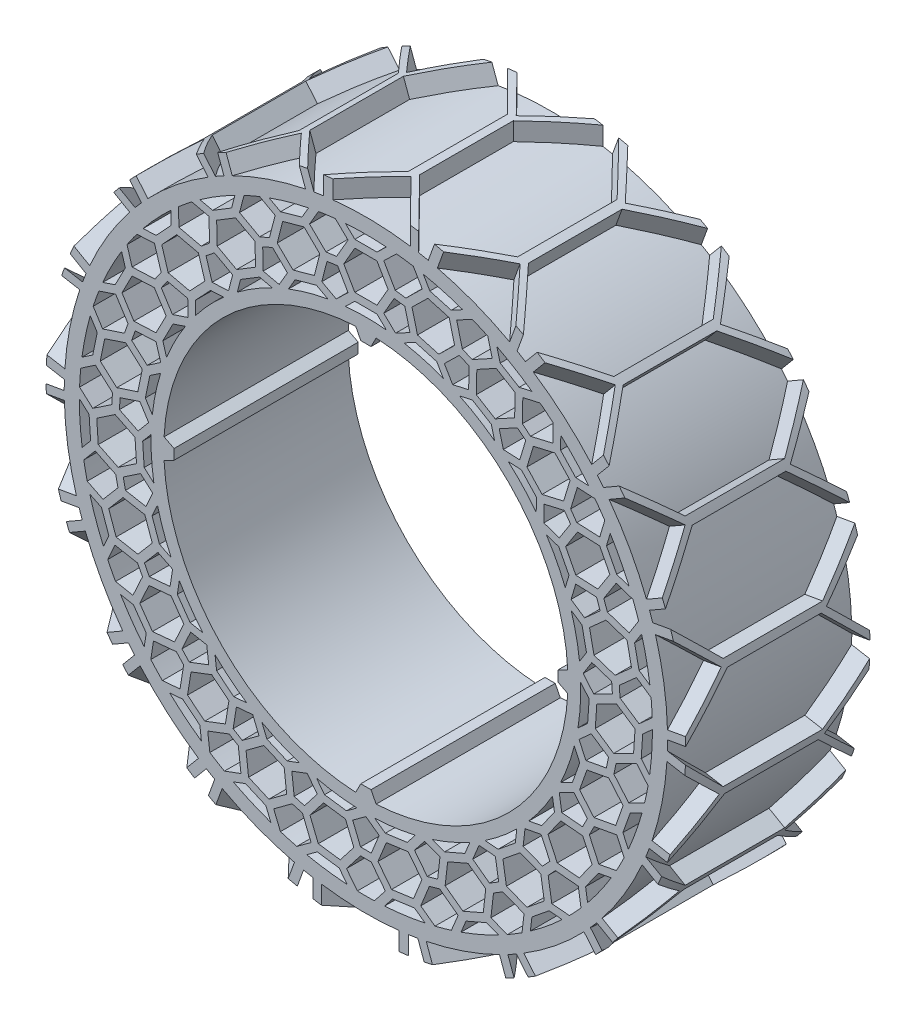
SolidWorks part; units mm, degrees
material "POLYURETHANE (11671)"
ref_plane "Front Plane" through (0, 0, 0) normal (0, 0, 1) x (1, 0, 0)
ref_plane "Top Plane" through (0, 0, 0) normal (0, 1, 0) x (1, 0, 0)
ref_plane "Right Plane" through (0, 0, 0) normal (1, 0, 0) x (0, 0, -1)
sketch "Sketch1" plane through (0, 0, 0) normal (0, 0, 1) x (1, 0, 0)
  line L0 (0, 120.3125) -> (0, 87.5) construction
  line L1 (5.083, 115.764) -> (7.5714, 120.074)
  line L2 (5.3125, 94.7047) -> (10.625, 103.9063)
  line L3 (10.625, 103.9063) -> (5.3125, 113.1078)
  line L4 (5.3125, 113.1078) -> (-5.3125, 113.1078)
  line L5 (-5.3125, 113.1078) -> (-10.625, 103.9062)
  line L6 (-10.625, 103.9062) -> (-5.3125, 94.7047)
  line L7 (-5.3125, 94.7047) -> (5.3125, 94.7047)
  line L12 (-5.542, 115.764) -> (5.083, 115.764)
  line L14 (8.0962, 87.1246) -> (5.2534, 92.0485)
  line L15 (5.2534, 92.0485) -> (-5.3716, 92.0485)
  line L16 (-5.3716, 92.0485) -> (-8.2212, 87.1129)
  line L19 (44.3701, 107.0441) -> (48.1825, 110.2431)
  line L20 (37.383, 87.1764) -> (45.5223, 94.006)
  line L21 (45.5223, 94.006) -> (43.6773, 104.4696)
  line L22 (43.6773, 104.4696) -> (33.693, 108.1035)
  line L23 (33.693, 108.1035) -> (25.5538, 101.2739)
  line L24 (25.5538, 101.2739) -> (27.3988, 90.8103)
  line L25 (27.3988, 90.8103) -> (37.383, 87.1764)
  line L27 (34.3859, 110.6781) -> (44.3701, 107.0441)
  line L28 (37.4063, 79.1013) -> (36.419, 84.7005)
  line L29 (36.419, 84.7005) -> (26.4348, 88.3345)
  line L30 (26.4348, 88.3345) -> (22.069, 84.6712)
  line L31 (41.1493, 113.0568) -> (29.9268, 82.2231) construction
  line L32 (78.3055, 85.4131) -> (82.9821, 87.1152)
  line L33 (64.9446, 69.1332) -> (74.9289, 72.7672)
  line L34 (74.9289, 72.7672) -> (76.7739, 83.2308)
  line L35 (76.7739, 83.2308) -> (68.6347, 90.0604)
  line L36 (68.6347, 90.0604) -> (58.6504, 86.4264)
  line L37 (58.6504, 86.4264) -> (56.8054, 75.9628)
  line L38 (56.8054, 75.9628) -> (64.9446, 69.1332)
  line L40 (70.1663, 92.2427) -> (78.3055, 85.4131)
  line L41 (62.2047, 61.5372) -> (63.192, 67.1364)
  line L42 (63.192, 67.1364) -> (55.0527, 73.966)
  line L43 (55.0527, 73.966) -> (49.6973, 72.0168)
  line L44 (77.3354, 92.1647) -> (56.2439, 67.0289) construction
  line L45 (102.7961, 53.48) -> (107.7729, 53.48)
  line L46 (84.673, 42.7516) -> (95.298, 42.7516)
  line L47 (95.298, 42.7516) -> (100.6105, 51.9531)
  line L48 (100.6105, 51.9531) -> (95.298, 61.1546)
  line L49 (95.298, 61.1546) -> (84.673, 61.1546)
  line L50 (84.673, 61.1546) -> (79.3605, 51.9531)
  line L51 (79.3605, 51.9531) -> (84.673, 42.7516)
  line L53 (97.4836, 62.6815) -> (102.7961, 53.48)
  line L54 (79.5002, 36.5508) -> (82.343, 41.4747)
  line L55 (82.343, 41.4747) -> (77.0305, 50.6762)
  line L56 (77.0305, 50.6762) -> (71.3314, 50.6762)
  line L57 (104.1937, 60.1563) -> (75.7772, 43.75) construction
  line L58 (114.888, 15.0964) -> (119.5646, 13.3942)
  line L59 (94.1885, 11.2135) -> (104.1727, 7.5795)
  line L60 (104.1727, 7.5795) -> (112.3119, 14.4092)
  line L61 (112.3119, 14.4092) -> (110.4669, 24.8727)
  line L62 (110.4669, 24.8727) -> (100.4827, 28.5067)
  line L63 (100.4827, 28.5067) -> (92.3434, 21.6771)
  line L64 (92.3434, 21.6771) -> (94.1885, 11.2135)
  line L66 (113.043, 25.56) -> (114.888, 15.0964)
  line L67 (87.2069, 7.1559) -> (91.5623, 10.8105)
  line L68 (91.5623, 10.8105) -> (89.7173, 21.2741)
  line L69 (89.7173, 21.2741) -> (84.3619, 23.2233)
  line L70 (118.4847, 20.892) -> (86.1707, 15.1942) construction
  line L71 (113.1226, -25.108) -> (116.9351, -28.307)
  line L72 (92.3434, -21.6771) -> (100.4827, -28.5067)
  line L73 (100.4827, -28.5067) -> (110.4669, -24.8727)
  line L74 (110.4669, -24.8727) -> (112.3119, -14.4092)
  line L75 (112.3119, -14.4092) -> (104.1727, -7.5795)
  line L76 (104.1727, -7.5795) -> (94.1885, -11.2135)
  line L77 (94.1885, -11.2135) -> (92.3434, -21.6771)
  line L79 (114.9677, -14.6444) -> (113.1226, -25.108)
  line L80 (84.3951, -23.1022) -> (89.7378, -21.1576)
  line L81 (89.7378, -21.1576) -> (91.5828, -10.694)
  line L82 (91.5828, -10.694) -> (87.2171, -7.0307)
  line L83 (118.4847, -20.892) -> (86.1707, -15.1942) construction
  line L84 (97.7131, -62.284) -> (100.2014, -66.594)
  line L85 (79.3605, -51.9531) -> (84.673, -61.1546)
  line L86 (84.673, -61.1546) -> (95.298, -61.1546)
  line L87 (95.298, -61.1546) -> (100.6105, -51.9531)
  line L88 (100.6105, -51.9531) -> (95.298, -42.7516)
  line L89 (95.298, -42.7516) -> (84.673, -42.7516)
  line L90 (84.673, -42.7516) -> (79.3605, -51.9531)
  line L92 (103.0256, -53.0825) -> (97.7131, -62.284)
  line L93 (71.4041, -50.5738) -> (77.0896, -50.5738)
  line L94 (77.0896, -50.5738) -> (82.4021, -41.3723)
  line L95 (82.4021, -41.3723) -> (79.5526, -36.4367)
  line L96 (104.1937, -60.1563) -> (75.7772, -43.75) construction
  line L97 (70.5178, -91.9477) -> (71.3821, -96.8489)
  line L98 (56.8054, -75.9628) -> (58.6504, -86.4264)
  line L99 (58.6504, -86.4264) -> (68.6347, -90.0604)
  line L100 (68.6347, -90.0604) -> (76.7739, -83.2308)
  line L101 (76.7739, -83.2308) -> (74.9289, -72.7672)
  line L102 (74.9289, -72.7672) -> (64.9446, -69.1332)
  line L103 (64.9446, -69.1332) -> (56.8054, -75.9628)
  line L105 (78.6571, -85.1181) -> (70.5178, -91.9477)
  line L106 (49.8006, -71.9455) -> (55.1433, -73.89)
  line L107 (55.1433, -73.89) -> (63.2825, -67.0604)
  line L108 (63.2825, -67.0604) -> (62.2929, -61.4479)
  line L109 (77.3354, -92.1647) -> (56.2439, -67.0289) construction
  line L110 (34.8171, -110.5211) -> (33.9529, -115.4223)
  line L111 (27.3988, -90.8103) -> (25.5538, -101.2739)
  line L112 (25.5538, -101.2739) -> (33.693, -108.1035)
  line L113 (33.693, -108.1035) -> (43.6773, -104.4696)
  line L114 (43.6773, -104.4696) -> (45.5223, -94.006)
  line L115 (45.5223, -94.006) -> (37.383, -87.1764)
  line L116 (37.383, -87.1764) -> (27.3988, -90.8103)
  line L118 (44.8014, -106.8871) -> (34.8171, -110.5211)
  line L119 (22.1905, -84.6394) -> (26.5459, -88.294)
  line L120 (26.5459, -88.294) -> (36.5301, -84.6601)
  line L121 (36.5301, -84.6601) -> (37.5197, -79.0476)
  line L122 (41.1493, -113.0568) -> (29.9268, -82.2231) construction
  line L123 (-5.083, -115.764) -> (-7.5714, -120.074)
  line L124 (-5.3125, -94.7047) -> (-10.625, -103.9063)
  line L125 (-10.625, -103.9063) -> (-5.3125, -113.1078)
  line L126 (-5.3125, -113.1078) -> (5.3125, -113.1078)
  line L127 (5.3125, -113.1078) -> (10.625, -103.9063)
  line L128 (10.625, -103.9063) -> (5.3125, -94.7047)
  line L129 (5.3125, -94.7047) -> (-5.3125, -94.7047)
  line L131 (5.542, -115.764) -> (-5.083, -115.764)
  line L132 (-8.0962, -87.1246) -> (-5.2534, -92.0485)
  line L133 (-5.2534, -92.0485) -> (5.3716, -92.0485)
  line L134 (5.3716, -92.0485) -> (8.2212, -87.1129)
  line L135 (0, -120.3125) -> (0, -87.5) construction
  line L136 (-44.3701, -107.0441) -> (-48.1825, -110.2431)
  line L137 (-37.383, -87.1764) -> (-45.5223, -94.006)
  line L138 (-45.5223, -94.006) -> (-43.6773, -104.4696)
  line L139 (-43.6773, -104.4696) -> (-33.693, -108.1035)
  line L140 (-33.693, -108.1035) -> (-25.5538, -101.2739)
  line L141 (-25.5538, -101.2739) -> (-27.3988, -90.8103)
  line L142 (-27.3988, -90.8103) -> (-37.383, -87.1764)
  line L144 (-34.3859, -110.6781) -> (-44.3701, -107.0441)
  line L145 (-37.4063, -79.1013) -> (-36.419, -84.7005)
  line L146 (-36.419, -84.7005) -> (-26.4348, -88.3345)
  line L147 (-26.4348, -88.3345) -> (-22.069, -84.6712)
  line L148 (-41.1493, -113.0568) -> (-29.9268, -82.2231) construction
  line L149 (-78.3055, -85.4131) -> (-82.9821, -87.1152)
  line L150 (-64.9446, -69.1332) -> (-74.9289, -72.7672)
  line L151 (-74.9289, -72.7672) -> (-76.7739, -83.2308)
  line L152 (-76.7739, -83.2308) -> (-68.6347, -90.0604)
  line L153 (-68.6347, -90.0604) -> (-58.6504, -86.4264)
  line L154 (-58.6504, -86.4264) -> (-56.8054, -75.9628)
  line L155 (-56.8054, -75.9628) -> (-64.9446, -69.1332)
  line L157 (-70.1663, -92.2427) -> (-78.3055, -85.4131)
  line L158 (-62.2047, -61.5372) -> (-63.192, -67.1364)
  line L159 (-63.192, -67.1364) -> (-55.0527, -73.966)
  line L160 (-55.0527, -73.966) -> (-49.6973, -72.0168)
  line L161 (-77.3354, -92.1647) -> (-56.2439, -67.0289) construction
  line L162 (-102.7961, -53.48) -> (-107.7729, -53.48)
  line L163 (-84.673, -42.7516) -> (-95.298, -42.7516)
  line L164 (-95.298, -42.7516) -> (-100.6105, -51.9531)
  line L165 (-100.6105, -51.9531) -> (-95.298, -61.1546)
  line L166 (-95.298, -61.1546) -> (-84.673, -61.1546)
  line L167 (-84.673, -61.1546) -> (-79.3605, -51.9531)
  line L168 (-79.3605, -51.9531) -> (-84.673, -42.7516)
  line L170 (-97.4836, -62.6815) -> (-102.7961, -53.48)
  line L171 (-79.5002, -36.5508) -> (-82.343, -41.4747)
  line L172 (-82.343, -41.4747) -> (-77.0305, -50.6762)
  line L173 (-77.0305, -50.6762) -> (-71.3314, -50.6762)
  line L174 (-104.1937, -60.1563) -> (-75.7772, -43.75) construction
  line L175 (-114.888, -15.0964) -> (-119.5646, -13.3942)
  line L176 (-94.1885, -11.2135) -> (-104.1727, -7.5795)
  line L177 (-104.1727, -7.5795) -> (-112.3119, -14.4092)
  line L178 (-112.3119, -14.4092) -> (-110.4669, -24.8727)
  line L179 (-110.4669, -24.8727) -> (-100.4827, -28.5067)
  line L180 (-100.4827, -28.5067) -> (-92.3434, -21.6771)
  line L181 (-92.3434, -21.6771) -> (-94.1885, -11.2135)
  line L183 (-113.043, -25.56) -> (-114.888, -15.0964)
  line L184 (-87.2069, -7.1559) -> (-91.5623, -10.8105)
  line L185 (-91.5623, -10.8105) -> (-89.7173, -21.2741)
  line L186 (-89.7173, -21.2741) -> (-84.3619, -23.2233)
  line L187 (-118.4847, -20.892) -> (-86.1707, -15.1942) construction
  line L188 (-113.1226, 25.108) -> (-116.9351, 28.307)
  line L189 (-92.3434, 21.6771) -> (-100.4827, 28.5067)
  line L190 (-100.4827, 28.5067) -> (-110.4669, 24.8727)
  line L191 (-110.4669, 24.8727) -> (-112.3119, 14.4092)
  line L192 (-112.3119, 14.4092) -> (-104.1727, 7.5795)
  line L193 (-104.1727, 7.5795) -> (-94.1885, 11.2135)
  line L194 (-94.1885, 11.2135) -> (-92.3434, 21.6771)
  line L196 (-114.9677, 14.6444) -> (-113.1226, 25.108)
  line L197 (-84.3951, 23.1022) -> (-89.7378, 21.1576)
  line L198 (-89.7378, 21.1576) -> (-91.5828, 10.694)
  line L199 (-91.5828, 10.694) -> (-87.2171, 7.0307)
  line L200 (-118.4847, 20.892) -> (-86.1707, 15.1942) construction
  line L201 (-97.7131, 62.284) -> (-100.2014, 66.594)
  line L202 (-79.3605, 51.9531) -> (-84.673, 61.1546)
  line L203 (-84.673, 61.1546) -> (-95.298, 61.1546)
  line L204 (-95.298, 61.1546) -> (-100.6105, 51.9531)
  line L205 (-100.6105, 51.9531) -> (-95.298, 42.7516)
  line L206 (-95.298, 42.7516) -> (-84.673, 42.7516)
  line L207 (-84.673, 42.7516) -> (-79.3605, 51.9531)
  line L209 (-103.0256, 53.0825) -> (-97.7131, 62.284)
  line L210 (-71.4041, 50.5738) -> (-77.0896, 50.5738)
  line L211 (-77.0896, 50.5738) -> (-82.4021, 41.3723)
  line L212 (-82.4021, 41.3723) -> (-79.5526, 36.4367)
  line L213 (-104.1937, 60.1562) -> (-75.7772, 43.75) construction
  line L214 (-70.5178, 91.9477) -> (-71.3821, 96.8489)
  line L215 (-56.8054, 75.9628) -> (-58.6504, 86.4264)
  line L216 (-58.6504, 86.4264) -> (-68.6347, 90.0604)
  line L217 (-68.6347, 90.0604) -> (-76.7739, 83.2308)
  line L218 (-76.7739, 83.2308) -> (-74.9289, 72.7672)
  line L219 (-74.9289, 72.7672) -> (-64.9446, 69.1332)
  line L220 (-64.9446, 69.1332) -> (-56.8054, 75.9628)
  line L222 (-78.6571, 85.1181) -> (-70.5178, 91.9477)
  line L223 (-49.8006, 71.9455) -> (-55.1433, 73.89)
  line L224 (-55.1433, 73.89) -> (-63.2825, 67.0604)
  line L225 (-63.2825, 67.0604) -> (-62.2929, 61.4479)
  line L226 (-77.3354, 92.1647) -> (-56.2439, 67.0289) construction
  line L227 (-34.8171, 110.5211) -> (-33.9529, 115.4223)
  line L228 (-27.3988, 90.8103) -> (-25.5538, 101.2739)
  line L229 (-25.5538, 101.2739) -> (-33.693, 108.1035)
  line L230 (-33.693, 108.1035) -> (-43.6773, 104.4696)
  line L231 (-43.6773, 104.4696) -> (-45.5223, 94.006)
  line L232 (-45.5223, 94.006) -> (-37.383, 87.1764)
  line L233 (-37.383, 87.1764) -> (-27.3988, 90.8103)
  line L235 (-44.8014, 106.8871) -> (-34.8171, 110.5211)
  line L236 (-22.1905, 84.6394) -> (-26.5459, 88.294)
  line L237 (-26.5459, 88.294) -> (-36.5301, 84.6601)
  line L238 (-36.5301, 84.6601) -> (-37.5197, 79.0476)
  line L239 (-41.1493, 113.0568) -> (-29.9268, 82.2231) construction
  line L240 (-25.5538, 101.2739) -> (-10.625, 103.9062) construction
  line L247 (-25.5538, 101.2739) -> (-6.7964, 89.5807) construction
  line L248 (-6.7964, 89.5807) -> (-10.625, 103.9062) construction
  line L249 (-10.625, 103.9062) -> (-22.9692, 85.2929) construction
  line L251 (-14.7311, 86.2511) -> (-17.7031, 103.9865) construction
  line L252 (-17.7031, 103.9865) -> (-26.9388, 90.0604) construction
  line L253 (-26.9388, 90.0604) -> (-7.9687, 99.3055) construction
  line L254 (-7.9687, 99.3055) -> (-5.3716, 93.9764) construction
  line L255 (-5.3716, 93.9764) -> (-26.4763, 96.0421) construction
  line L257 (-14.3347, 86.3178) -> (-6.7191, 93.9229)
  line L258 (-6.7191, 93.9229) -> (-11.8222, 103.9556)
  line L259 (-11.8222, 103.9556) -> (-22.9409, 102.2025)
  line L260 (-22.9409, 102.2025) -> (-24.7095, 91.0863)
  line L261 (-24.7095, 91.0863) -> (-15.1082, 86.1858)
  line L262 (-8.8671, 116.6558) -> (-11.3652, 119.7745)
  line L265 (-30.5411, 113.3409) -> (-23.6873, 104.7845)
  line L266 (-23.6873, 104.7845) -> (-12.8502, 106.4419)
  line L267 (-12.8502, 106.4419) -> (-8.8671, 116.6558)
  line L269 (31.5663, 112.6533) -> (30.2854, 116.4383)
  line L270 (24.33, 104.4177) -> (31.5663, 112.6533)
  line L271 (13.5797, 106.5667) -> (24.33, 104.4177)
  line L272 (10.0656, 116.9513) -> (13.5797, 106.5667)
  line L273 (16.0522, 86.015) -> (25.8096, 90.5567)
  line L274 (25.8096, 90.5567) -> (24.4457, 101.7297)
  line L275 (24.4457, 101.7297) -> (13.398, 103.8852)
  line L276 (13.398, 103.8852) -> (7.9341, 94.0443)
  line L277 (7.9341, 94.0443) -> (15.2802, 86.1555)
  line L280 (68.1923, 95.0632) -> (68.2833, 99.058)
  line L281 (58.5757, 89.7992) -> (68.1923, 95.0632)
  line L282 (49.2087, 95.4955) -> (58.5757, 89.7992)
  line L283 (49.4583, 106.4557) -> (49.2087, 95.4955)
  line L284 (44.503, 75.3375) -> (55.2253, 76.268)
  line L285 (55.2253, 76.268) -> (57.765, 87.2338)
  line L286 (57.765, 87.2338) -> (48.1208, 93.0378)
  line L287 (48.1208, 93.0378) -> (39.6206, 85.6591)
  line L288 (39.6206, 85.6591) -> (43.8256, 75.7335)
  line L291 (96.5933, 66.007) -> (98.0451, 69.7298)
  line L292 (85.7563, 64.3496) -> (96.5933, 66.007)
  line L293 (78.9024, 72.906) -> (85.7563, 64.3496)
  line L294 (82.8856, 83.1199) -> (78.9024, 72.906)
  line L295 (67.5861, 55.5732) -> (77.98, 52.7803)
  line L296 (77.98, 52.7803) -> (84.1171, 62.2161)
  line L297 (84.1171, 62.2161) -> (77.0396, 70.9686)
  line L298 (77.0396, 70.9686) -> (66.5283, 66.9422)
  line L299 (66.5283, 66.9422) -> (67.085, 56.177)
  line L302 (113.3438, 28.9894) -> (115.9813, 31.9912)
  line L303 (102.5934, 31.1385) -> (113.3438, 28.9894)
  line L304 (99.0793, 41.523) -> (102.5934, 31.1385)
  line L305 (106.3156, 49.7586) -> (99.0793, 41.523)
  line L306 (82.5173, 29.1059) -> (91.3292, 22.9265)
  line L307 (91.3292, 22.9265) -> (100.3234, 29.6943)
  line L308 (100.3234, 29.6943) -> (96.6662, 40.3396)
  line L309 (96.6662, 40.3396) -> (85.4118, 40.151)
  line L310 (85.4118, 40.151) -> (82.2529, 29.8447)
  line L313 (116.4233, -11.5247) -> (119.9284, -9.606)
  line L314 (107.0563, -5.8284) -> (116.4233, -11.5247)
  line L315 (107.3058, 5.1318) -> (107.0563, -5.8284)
  line L316 (116.9224, 10.3957) -> (107.3058, 5.1318)
  line L317 (87.4957, -0.872) -> (93.6627, -9.6925)
  line L318 (93.6627, -9.6925) -> (104.4292, -6.4091)
  line L319 (104.4292, -6.4091) -> (104.6335, 4.8451)
  line L320 (104.6335, 4.8451) -> (93.9933, 8.5171)
  line L321 (93.9933, 8.5171) -> (87.5, -0.0873)
  line L324 (105.4604, -50.6488) -> (109.4104, -50.0447)
  line L325 (98.6065, -42.0923) -> (105.4604, -50.6488)
  line L326 (102.5897, -31.8785) -> (98.6065, -42.0923)
  line L327 (113.4267, -30.2211) -> (102.5897, -31.8785)
  line L328 (81.9208, -30.7447) -> (84.6991, -41.1425)
  line L329 (84.6991, -41.1425) -> (95.9393, -41.7395)
  line L330 (95.9393, -41.7395) -> (99.9804, -31.2339)
  line L331 (99.9804, -31.2339) -> (91.2378, -24.1441)
  line L332 (91.2378, -24.1441) -> (82.1932, -30.0088)
  line L335 (81.7775, -83.6639) -> (85.6958, -84.4471)
  line L336 (78.2634, -73.2793) -> (81.7775, -83.6639)
  line L337 (85.4997, -65.0437) -> (78.2634, -73.2793)
  line L338 (96.25, -67.1927) -> (85.4997, -65.0437)
  line L339 (66.4651, -56.9091) -> (65.5196, -67.6301)
  line L340 (65.5196, -67.6301) -> (75.8777, -72.0354)
  line L341 (75.8777, -72.0354) -> (83.2682, -63.5456)
  line L342 (83.2682, -63.5456) -> (77.4777, -53.8932)
  line L343 (77.4777, -53.8932) -> (66.9727, -56.3108)
  line L346 (48.231, -106.5879) -> (51.6451, -108.6641)
  line L347 (48.4806, -95.6277) -> (48.231, -106.5879)
  line L348 (58.0972, -90.3637) -> (48.4806, -95.6277)
  line L349 (67.4642, -96.06) -> (58.0972, -90.3637)
  line L350 (42.9927, -76.2094) -> (38.4374, -85.9606)
  line L351 (38.4374, -85.9606) -> (46.6641, -93.6429)
  line L352 (46.6641, -93.6429) -> (56.5127, -88.1927)
  line L353 (56.5127, -88.1927) -> (54.3727, -77.142)
  line L354 (54.3727, -77.142) -> (43.6743, -75.8208)
  line L357 (8.8671, -116.6558) -> (11.3652, -119.7745)
  line L358 (12.8502, -106.4419) -> (8.8671, -116.6558)
  line L359 (23.6873, -104.7845) -> (12.8502, -106.4419)
  line L360 (30.5411, -113.3409) -> (23.6873, -104.7845)
  line L361 (14.3347, -86.3178) -> (6.7191, -93.9229)
  line L362 (6.7191, -93.9229) -> (11.8222, -103.9556)
  line L363 (11.8222, -103.9556) -> (22.9409, -102.2025)
  line L364 (22.9409, -102.2025) -> (24.7095, -91.0863)
  line L365 (24.7095, -91.0863) -> (15.1082, -86.1858)
  line L368 (-31.5663, -112.6533) -> (-30.2854, -116.4383)
  line L369 (-24.33, -104.4177) -> (-31.5663, -112.6533)
  line L370 (-13.5797, -106.5667) -> (-24.33, -104.4177)
  line L371 (-10.0656, -116.9513) -> (-13.5797, -106.5667)
  line L372 (-16.0522, -86.015) -> (-25.8096, -90.5567)
  line L373 (-25.8096, -90.5567) -> (-24.4457, -101.7297)
  line L374 (-24.4457, -101.7297) -> (-13.398, -103.8852)
  line L375 (-13.398, -103.8852) -> (-7.9341, -94.0443)
  line L376 (-7.9341, -94.0443) -> (-15.2802, -86.1555)
  line L379 (-68.1923, -95.0632) -> (-68.2833, -99.058)
  line L380 (-58.5757, -89.7992) -> (-68.1923, -95.0632)
  line L381 (-49.2087, -95.4955) -> (-58.5757, -89.7992)
  line L382 (-49.4583, -106.4557) -> (-49.2087, -95.4955)
  line L383 (-44.503, -75.3375) -> (-55.2253, -76.268)
  line L384 (-55.2253, -76.268) -> (-57.765, -87.2338)
  line L385 (-57.765, -87.2338) -> (-48.1208, -93.0378)
  line L386 (-48.1208, -93.0378) -> (-39.6206, -85.6591)
  line L387 (-39.6206, -85.6591) -> (-43.8256, -75.7335)
  line L390 (-96.5933, -66.007) -> (-98.0451, -69.7298)
  line L391 (-85.7563, -64.3496) -> (-96.5933, -66.007)
  line L392 (-78.9024, -72.906) -> (-85.7563, -64.3496)
  line L393 (-82.8856, -83.1199) -> (-78.9024, -72.906)
  line L394 (-67.5861, -55.5732) -> (-77.98, -52.7803)
  line L395 (-77.98, -52.7803) -> (-84.1171, -62.2161)
  line L396 (-84.1171, -62.2161) -> (-77.0396, -70.9686)
  line L397 (-77.0396, -70.9686) -> (-66.5283, -66.9422)
  line L398 (-66.5283, -66.9422) -> (-67.085, -56.177)
  line L401 (-113.3438, -28.9894) -> (-115.9813, -31.9912)
  line L402 (-102.5934, -31.1385) -> (-113.3438, -28.9894)
  line L403 (-99.0793, -41.523) -> (-102.5934, -31.1385)
  line L404 (-106.3156, -49.7586) -> (-99.0793, -41.523)
  line L405 (-82.5173, -29.1059) -> (-91.3292, -22.9265)
  line L406 (-91.3292, -22.9265) -> (-100.3234, -29.6943)
  line L407 (-100.3234, -29.6943) -> (-96.6662, -40.3396)
  line L408 (-96.6662, -40.3396) -> (-85.4118, -40.151)
  line L409 (-85.4118, -40.151) -> (-82.2529, -29.8447)
  line L412 (-116.4233, 11.5247) -> (-119.9284, 9.606)
  line L413 (-107.0563, 5.8284) -> (-116.4233, 11.5247)
  line L414 (-107.3058, -5.1318) -> (-107.0563, 5.8284)
  line L415 (-116.9224, -10.3957) -> (-107.3058, -5.1318)
  line L416 (-87.4957, 0.872) -> (-93.6627, 9.6925)
  line L417 (-93.6627, 9.6925) -> (-104.4292, 6.4091)
  line L418 (-104.4292, 6.4091) -> (-104.6335, -4.8451)
  line L419 (-104.6335, -4.8451) -> (-93.9933, -8.5171)
  line L420 (-93.9933, -8.5171) -> (-87.5, 0.0873)
  line L423 (-105.4604, 50.6488) -> (-109.4104, 50.0447)
  line L424 (-98.6065, 42.0923) -> (-105.4604, 50.6488)
  line L425 (-102.5897, 31.8785) -> (-98.6065, 42.0923)
  line L426 (-113.4267, 30.2211) -> (-102.5897, 31.8785)
  line L427 (-81.9208, 30.7447) -> (-84.6991, 41.1425)
  line L428 (-84.6991, 41.1425) -> (-95.9393, 41.7395)
  line L429 (-95.9393, 41.7395) -> (-99.9804, 31.2339)
  line L430 (-99.9804, 31.2339) -> (-91.2378, 24.1441)
  line L431 (-91.2378, 24.1441) -> (-82.1932, 30.0088)
  line L434 (-81.7775, 83.6639) -> (-85.6958, 84.4471)
  line L435 (-78.2634, 73.2793) -> (-81.7775, 83.6639)
  line L436 (-85.4997, 65.0437) -> (-78.2634, 73.2793)
  line L437 (-96.25, 67.1927) -> (-85.4997, 65.0437)
  line L438 (-66.4651, 56.9091) -> (-65.5196, 67.6301)
  line L439 (-65.5196, 67.6301) -> (-75.8777, 72.0354)
  line L440 (-75.8777, 72.0354) -> (-83.2682, 63.5456)
  line L441 (-83.2682, 63.5456) -> (-77.4777, 53.8932)
  line L442 (-77.4777, 53.8932) -> (-66.9727, 56.3108)
  line L445 (-48.231, 106.5879) -> (-51.6451, 108.6641)
  line L446 (-48.4806, 95.6277) -> (-48.231, 106.5879)
  line L447 (-58.0972, 90.3637) -> (-48.4806, 95.6277)
  line L448 (-67.4642, 96.06) -> (-58.0972, 90.3637)
  line L449 (-42.9927, 76.2094) -> (-38.4374, 85.9606)
  line L450 (-38.4374, 85.9606) -> (-46.6641, 93.6429)
  line L451 (-46.6641, 93.6429) -> (-56.5127, 88.1927)
  line L452 (-56.5127, 88.1927) -> (-54.3727, 77.142)
  line L453 (-54.3727, 77.142) -> (-43.6743, 75.8208)
  line L455 (-29.228, 116.7083) -> (-30.5411, 113.3409)
  line L457 (-8.0138, 120.0453) -> (-5.542, 115.764)
  line L459 (12.4513, 119.6665) -> (10.0656, 116.9513)
  line L461 (33.5274, 115.5466) -> (34.3859, 110.6781)
  line L463 (52.6287, 108.1911) -> (49.4583, 106.4557)
  line L465 (71.0247, 97.1112) -> (70.1663, 92.2427)
  line L467 (86.4584, 83.6663) -> (82.8856, 83.1199)
  line L469 (99.9554, 66.9628) -> (97.4836, 62.6815)
  line L471 (109.8598, 49.0501) -> (106.3156, 49.7586)
  line L473 (116.83, 28.7377) -> (113.043, 25.56)
  line L475 (120.0106, 8.5177) -> (116.9224, 10.3957)
  line L477 (119.6131, -12.9536) -> (114.9677, -14.6444)
  line L479 (115.6863, -33.042) -> (113.4267, -30.2211)
  line L481 (107.9692, -53.0825) -> (103.0256, -53.0825)
  line L483 (97.4086, -70.6164) -> (96.25, -67.1927)
  line L485 (83.3025, -86.8089) -> (78.6571, -85.1181)
  line L487 (67.3819, -99.6734) -> (67.4642, -96.06)
  line L488 (-86.4584, -83.6663) -> (-82.8856, -83.1199)
  line L489 (48.5884, -110.0648) -> (44.8014, -106.8871)
  line L491 (29.228, -116.7083) -> (30.5411, -113.3409)
  line L492 (-52.6287, -108.1911) -> (-49.4583, -106.4557)
  line L493 (8.0138, -120.0453) -> (5.542, -115.764)
  line L495 (-12.4513, -119.6665) -> (-10.0656, -116.9513)
  line L496 (-71.0247, -97.1112) -> (-70.1663, -92.2427)
  line L497 (-33.5274, -115.5466) -> (-34.3859, -110.6781)
  line L508 (-99.9554, -66.9628) -> (-97.4836, -62.6815)
  line L510 (-109.8598, -49.0501) -> (-106.3156, -49.7586)
  line L512 (-116.83, -28.7377) -> (-113.043, -25.56)
  line L514 (-120.0106, -8.5177) -> (-116.9224, -10.3957)
  line L516 (-119.6131, 12.9536) -> (-114.9677, 14.6444)
  line L518 (-115.6863, 33.042) -> (-113.4267, 30.2211)
  line L520 (-107.9692, 53.0825) -> (-103.0256, 53.0825)
  line L522 (-97.4086, 70.6164) -> (-96.25, 67.1927)
  line L524 (-83.3025, 86.8089) -> (-78.6571, 85.1181)
  line L526 (-67.3819, 99.6734) -> (-67.4642, 96.06)
  line L528 (-48.5884, 110.0648) -> (-44.8014, 106.8871)
  arc A2 (-11.3652, 119.7745) -> (-29.228, 116.7083) centre (0, 0) ccw
  arc A3 (-22.1905, 84.6394) -> (-37.5197, 79.0476) centre (0, 0) ccw
  circle A4 centre (0, 103.9062) radius 9.2015 construction
  circle A5 centre (35.538, 97.6399) radius 9.2015 construction
  circle A6 centre (66.7897, 79.5968) radius 9.2015 construction
  circle A7 centre (89.9855, 51.9531) radius 9.2015 construction
  circle A8 centre (102.3277, 18.0431) radius 9.2015 construction
  circle A9 centre (102.3277, -18.0431) radius 9.2015 construction
  circle A10 centre (89.9855, -51.9531) radius 9.2015 construction
  circle A11 centre (66.7897, -79.5968) radius 9.2015 construction
  circle A12 centre (35.538, -97.6399) radius 9.2015 construction
  circle A13 centre (0, -103.9063) radius 9.2015 construction
  circle A14 centre (-35.538, -97.6399) radius 9.2015 construction
  circle A15 centre (-66.7897, -79.5968) radius 9.2015 construction
  circle A16 centre (-89.9855, -51.9531) radius 9.2015 construction
  circle A17 centre (-102.3277, -18.0431) radius 9.2015 construction
  circle A18 centre (-102.3277, 18.0431) radius 9.2015 construction
  circle A19 centre (-89.9855, 51.9531) radius 9.2015 construction
  circle A20 centre (-66.7897, 79.5968) radius 9.2015 construction
  circle A21 centre (-35.538, 97.6399) radius 9.2015 construction
  circle A22 centre (0, 0) radius 82.8125
  circle A23 centre (-16.1751, 95.4273) radius 7.7463 construction
  arc A24 (12.6499, 119.6456) -> (30.1625, 116.4702) centre (20.8159, 114.8023) ccw construction
  circle A25 centre (17.4384, 95.2045) radius 7.7463 construction
  arc A26 (52.8083, 108.1036) -> (68.1787, 99.13) centre (58.8253, 100.7594) ccw construction
  circle A27 centre (48.9487, 83.4987) radius 7.7463 construction
  arc A28 (86.5972, 83.5226) -> (97.9715, 69.8333) centre (89.7394, 74.5634) ccw construction
  circle A29 centre (74.5549, 61.7217) radius 7.7463 construction
  arc A30 (109.9411, 48.8676) -> (115.9475, 32.1136) centre (109.8297, 39.374) ccw construction
  circle A31 centre (91.1688, 32.5001) radius 7.7463 construction
  arc A32 (120.0246, 8.3185) -> (119.9385, -9.4795) centre (116.6729, -0.5645) ccw construction
  circle A33 centre (96.7863, -0.6414) radius 7.7463 construction
  arc A34 (115.6313, -33.234) -> (109.4631, -49.9292) centre (109.4436, -40.4349) ccw construction
  circle A35 centre (90.73, -33.7056) radius 7.7463 construction
  arc A36 (97.2912, -70.778) -> (85.7849, -84.3567) centre (89.0138, -75.4283) ccw construction
  circle A37 centre (73.7303, -62.7044) radius 7.7463 construction
  arc A38 (67.2163, -99.7851) -> (51.7598, -108.6095) centre (57.8476, -101.3239) ccw construction
  circle A39 centre (47.8377, -84.1401) radius 7.7463 construction
  arc A40 (29.0342, -116.7567) -> (11.4916, -119.7624) centre (19.7041, -114.9984) ccw construction
  circle A41 centre (16.1751, -95.4273) radius 7.7463 construction
  arc A42 (-12.6499, -119.6456) -> (-30.1625, -116.4702) centre (-20.8159, -114.8023) ccw construction
  circle A43 centre (-17.4384, -95.2045) radius 7.7463 construction
  arc A44 (-52.8083, -108.1036) -> (-68.1787, -99.13) centre (-58.8253, -100.7594) ccw construction
  circle A45 centre (-48.9487, -83.4987) radius 7.7463 construction
  arc A46 (-86.5972, -83.5226) -> (-97.9715, -69.8333) centre (-89.7394, -74.5634) ccw construction
  circle A47 centre (-74.5549, -61.7217) radius 7.7463 construction
  arc A48 (-109.9411, -48.8676) -> (-115.9475, -32.1136) centre (-109.8297, -39.374) ccw construction
  circle A49 centre (-91.1688, -32.5001) radius 7.7463 construction
  arc A50 (-120.0246, -8.3185) -> (-119.9385, 9.4795) centre (-116.6729, 0.5645) ccw construction
  circle A51 centre (-96.7863, 0.6414) radius 7.7463 construction
  arc A52 (-115.6313, 33.234) -> (-109.4631, 49.9292) centre (-109.4436, 40.4349) ccw construction
  circle A53 centre (-90.73, 33.7056) radius 7.7463 construction
  arc A54 (-97.2912, 70.778) -> (-85.7849, 84.3567) centre (-89.0138, 75.4283) ccw construction
  circle A55 centre (-73.7303, 62.7044) radius 7.7463 construction
  arc A56 (-67.2163, 99.7851) -> (-51.7598, 108.6095) centre (-57.8476, 101.3239) ccw construction
  circle A57 centre (-47.8377, 84.1401) radius 7.7463 construction
  arc A58 (7.5714, 120.074) -> (-8.0138, 120.0453) centre (0, 0) ccw
  arc A59 (30.2854, 116.4383) -> (12.4513, 119.6665) centre (0, 0) ccw
  arc A60 (48.1825, 110.2431) -> (33.5274, 115.5466) centre (0, 0) ccw
  arc A61 (68.2833, 99.058) -> (52.6287, 108.1911) centre (0, 0) ccw
  arc A62 (82.9821, 87.1152) -> (71.0247, 97.1112) centre (0, 0) ccw
  arc A63 (98.0451, 69.7298) -> (86.4584, 83.6663) centre (0, 0) ccw
  arc A64 (107.7729, 53.48) -> (99.9554, 66.9628) centre (0, 0) ccw
  arc A65 (115.9813, 31.9912) -> (109.8598, 49.0501) centre (0, 0) ccw
  arc A66 (119.5646, 13.3942) -> (116.83, 28.7377) centre (0, 0) ccw
  arc A67 (119.9284, -9.606) -> (120.0106, 8.5177) centre (0, 0) ccw
  arc A68 (116.9351, -28.307) -> (119.6131, -12.9536) centre (0, 0) ccw
  arc A69 (109.4104, -50.0447) -> (115.6863, -33.042) centre (0, 0) ccw
  arc A70 (100.2014, -66.594) -> (107.9692, -53.0825) centre (0, 0) ccw
  arc A71 (85.6958, -84.4471) -> (97.4086, -70.6164) centre (0, 0) ccw
  arc A72 (71.3821, -96.8489) -> (83.3025, -86.8089) centre (0, 0) ccw
  arc A73 (51.6451, -108.6641) -> (67.3819, -99.6734) centre (0, 0) ccw
  arc A74 (33.9529, -115.4223) -> (48.5884, -110.0648) centre (0, 0) ccw
  arc A75 (11.3652, -119.7745) -> (29.228, -116.7083) centre (0, 0) ccw
  arc A76 (-7.5714, -120.074) -> (8.0138, -120.0453) centre (0, 0) ccw
  arc A77 (-30.2854, -116.4383) -> (-12.4513, -119.6665) centre (0, 0) ccw
  arc A78 (-48.1825, -110.2431) -> (-33.5274, -115.5466) centre (0, 0) ccw
  arc A79 (-68.2833, -99.058) -> (-52.6287, -108.1911) centre (0, 0) ccw
  arc A80 (-82.9821, -87.1152) -> (-71.0247, -97.1112) centre (0, 0) ccw
  arc A81 (-98.0451, -69.7298) -> (-86.4584, -83.6663) centre (0, 0) ccw
  arc A82 (-107.7729, -53.48) -> (-99.9554, -66.9628) centre (0, 0) ccw
  arc A83 (-115.9813, -31.9912) -> (-109.8598, -49.0501) centre (0, 0) ccw
  arc A84 (-119.5646, -13.3942) -> (-116.83, -28.7377) centre (0, 0) ccw
  arc A85 (-119.9284, 9.606) -> (-120.0106, -8.5177) centre (0, 0) ccw
  arc A86 (-116.9351, 28.307) -> (-119.6131, 12.9536) centre (0, 0) ccw
  arc A87 (-109.4104, 50.0447) -> (-115.6863, 33.042) centre (0, 0) ccw
  arc A88 (-100.2014, 66.594) -> (-107.9692, 53.0825) centre (0, 0) ccw
  arc A89 (-85.6958, 84.4471) -> (-97.4086, 70.6164) centre (0, 0) ccw
  arc A90 (-71.3821, 96.8489) -> (-83.3025, 86.8089) centre (0, 0) ccw
  arc A91 (-51.6451, 108.6641) -> (-67.3819, 99.6734) centre (0, 0) ccw
  arc A92 (-33.9529, 115.4223) -> (-48.5884, 110.0648) centre (0, 0) ccw
  arc A93 (-14.3347, 86.3178) -> (-15.1082, 86.1858) centre (0, 0) ccw
  arc A94 (8.0962, 87.1246) -> (-8.2212, 87.1129) centre (0, 0) ccw
  arc A95 (16.0522, 86.015) -> (15.2802, 86.1555) centre (0, 0) ccw
  arc A96 (37.4063, 79.1013) -> (22.069, 84.6712) centre (0, 0) ccw
  arc A97 (44.503, 75.3375) -> (43.8256, 75.7335) centre (0, 0) ccw
  arc A98 (62.2047, 61.5372) -> (49.6973, 72.0168) centre (0, 0) ccw
  arc A99 (67.5861, 55.5732) -> (67.085, 56.177) centre (0, 0) ccw
  arc A100 (79.5002, 36.5508) -> (71.3314, 50.6762) centre (0, 0) ccw
  arc A101 (82.5173, 29.1059) -> (82.2529, 29.8447) centre (0, 0) ccw
  arc A102 (87.2069, 7.1559) -> (84.3619, 23.2233) centre (0, 0) ccw
  arc A103 (87.4957, -0.872) -> (87.5, -0.0873) centre (0, 0) ccw
  arc A104 (84.3951, -23.1022) -> (87.2171, -7.0307) centre (0, 0) ccw
  arc A105 (81.9208, -30.7447) -> (82.1932, -30.0088) centre (0, 0) ccw
  arc A106 (71.4041, -50.5738) -> (79.5526, -36.4367) centre (0, 0) ccw
  arc A107 (66.4651, -56.9091) -> (66.9727, -56.3108) centre (0, 0) ccw
  arc A108 (49.8006, -71.9455) -> (62.2929, -61.4479) centre (0, 0) ccw
  arc A109 (42.9927, -76.2094) -> (43.6743, -75.8208) centre (0, 0) ccw
  arc A110 (22.1905, -84.6394) -> (37.5197, -79.0476) centre (0, 0) ccw
  arc A111 (14.3347, -86.3178) -> (15.1082, -86.1858) centre (0, 0) ccw
  arc A112 (-8.0962, -87.1246) -> (8.2212, -87.1129) centre (0, 0) ccw
  arc A113 (-16.0522, -86.015) -> (-15.2802, -86.1555) centre (0, 0) ccw
  arc A114 (-37.4063, -79.1013) -> (-22.069, -84.6712) centre (0, 0) ccw
  arc A115 (-44.503, -75.3375) -> (-43.8256, -75.7335) centre (0, 0) ccw
  arc A116 (-62.2047, -61.5372) -> (-49.6973, -72.0168) centre (0, 0) ccw
  arc A117 (-67.5861, -55.5732) -> (-67.085, -56.177) centre (0, 0) ccw
  arc A118 (-79.5002, -36.5508) -> (-71.3314, -50.6762) centre (0, 0) ccw
  arc A119 (-82.5173, -29.1059) -> (-82.2529, -29.8447) centre (0, 0) ccw
  arc A120 (-87.2069, -7.1559) -> (-84.3619, -23.2233) centre (0, 0) ccw
  arc A121 (-87.4957, 0.872) -> (-87.5, 0.0873) centre (0, 0) ccw
  arc A122 (-84.3951, 23.1022) -> (-87.2171, 7.0307) centre (0, 0) ccw
  arc A123 (-81.9208, 30.7447) -> (-82.1932, 30.0088) centre (0, 0) ccw
  arc A124 (-71.4041, 50.5738) -> (-79.5526, 36.4367) centre (0, 0) ccw
  arc A125 (-66.4651, 56.9091) -> (-66.9727, 56.3108) centre (0, 0) ccw
  arc A126 (-49.8006, 71.9455) -> (-62.2929, 61.4479) centre (0, 0) ccw
  arc A127 (-42.9927, 76.2094) -> (-43.6743, 75.8208) centre (0, 0) ccw
  circle A128 centre (0, 0) radius 125
  point P8 (0, 103.9062)
  point P9 (0, 94.7047)
  point P35 (35.538, 97.6399)
  point P54 (66.7897, 79.5968)
  point P73 (89.9855, 51.9531)
  point P92 (102.3277, 18.0431)
  point P111 (102.3277, -18.0431)
  point P130 (89.9855, -51.9531)
  point P149 (66.7897, -79.5968)
  point P168 (35.538, -97.6399)
  point P187 (0, -103.9063)
  point P206 (-35.538, -97.6399)
  point P225 (-66.7897, -79.5968)
  point P244 (-89.9855, -51.9531)
  point P263 (-102.3277, -18.0431)
  point P282 (-102.3277, 18.0431)
  point P301 (-89.9855, 51.9531)
  point P320 (-66.7897, 79.5968)
  point P339 (-35.538, 97.6399)
  point P356 (0, 0)
  point P635 (0, 0)
  dimension "D1" = 250
  dimension "D2" = 165.625
  dimension "D3" = 18.403
  dimension "D8" = 18
  dimension "D9" = 18
extrude "Boss-Extrude2" add sketch "Sketch1" along normal blind 80
sketch "Sketch3" plane through (0, 0, 0) normal (0, 1, 0) x (1, 0, 0)
  line L43 (-125, 0) -> (-125, -41.2071) construction
  line L44 (-125, 0) -> (-125, -80) construction
  line L45 (0, -20.6035) -> (0, -60.6035)
  line L46 (-125, -41.2071) -> (-125, -80) construction
  line L47 (125, 0) -> (-125, 0) construction
  line L48 (-125, -41.2071) -> (125, -41.2071) construction
  line L49 (125, 0) -> (125, -41.2071) construction
  line L50 (125, -41.2071) -> (125, -80) construction
  line L51 (-125, -20.6035) -> (125, -20.6035) construction
  line L52 (-125, -60.6035) -> (125, -60.6035) construction
  line L69 (0, -20.6035) -> (20.1873, 0)
  line L70 (20.1873, 0) -> (23.6873, 0)
  line L71 (23.6873, 0) -> (3.5, -20.6035)
  line L72 (3.5, -20.6035) -> (3.5, -60.6035)
  line L73 (3.5, -60.6035) -> (-15.5046, -80)
  line L74 (-125, -80) -> (125, -80) construction
  line L75 (0, -60.6035) -> (-19.3965, -80)
  line L76 (-19.3965, -80) -> (-15.5046, -80)
  dimension "D1" = 2.5
  dimension "D2" = 3.5
  dimension "D3" = 45
extrude "Boss-Extrude3" add sketch "Sketch3" along normal blind 12 from offset 122
sketch "Sketch4" plane through (0, 0, 0) normal (1, 0, 0) x (0, 0, -1)
  line L0 (0, 0) -> (-115.3186, 0) construction
pattern_circular "CirPattern1" count 18 over 360 about axis through (0, 0, 0) along (0, 0, 1) of "Boss-Extrude3" reverse direction yes
sketch "Sketch5" plane through (0, 0, 0) normal (0, 0, 1) x (1, 0, 0)
  circle A0 centre (0, 0) radius 132.5
  circle A1 centre (0, 0) radius 140
  dimension "D1" = 265
  dimension "D2" = 280
extrude "Cut-Extrude1" cut sketch "Sketch5" along normal through all contours A1 | A0
sketch "Sketch6" plane through (0, 0, 0) normal (0, 1, 0) x (1, 0, 0)
  line L0 (-15.5046, -80) -> (24.008, -80) construction
  line L4 (0, 0) -> (0, -80)
  line L5 (0, -80) -> (-5, -80)
  line L6 (-5, -80) -> (-5, 0)
  line L7 (20.1873, 0) -> (-19.7191, 0) construction
  line L8 (-5, 0) -> (0, 0)
  dimension "D1" = 5
extrude "Boss-Extrude4" add sketch "Sketch6" against normal blind 3 from offset 82.9
pattern_circular "CirPattern2" count 4 over 360 about axis through (0, 0, 0) along (0, 0, 1) of "Boss-Extrude4"
sketch "Sketch7" plane through (0, 0, 0) normal (0, 0, 1) x (1, 0, 0)
  circle A0 centre (0, 0) radius 80.3125
  dimension "D1" = 160.625
extrude "Cut-Extrude3" cut sketch "Sketch7" along normal blind 80 contours A0
scale "Scale1" bodies to scale 198 scale about centroid uniform scaling yes scale factor 0.471698
sketch "Sketch10" plane through (0, 0, 58.8765) normal (0, 0, 1) x (1, 0, 0)
  circle A0 centre (0, 0) radius 39.5
  dimension "D1" = 79
extrude "Cut-Extrude4" cut sketch "Sketch10" against normal through all
sketch "Sketch11" plane through (0, 0, 58.8765) normal (0, 0, 1) x (1, 0, 0)
  line L0 (-2, 39.4493) -> (-1, 37.5)
  line L5 (-1, 37.5) -> (1, 37.5)
  line L6 (1, 37.5) -> (2, 39.4493)
  line L7 (37.5, -1) -> (39.4493, -2)
  line L8 (37.5, 1) -> (37.5, -1)
  line L9 (39.4493, 2) -> (37.5, 1)
  line L10 (-1, -37.5) -> (-2, -39.4493)
  line L11 (1, -37.5) -> (-1, -37.5)
  line L12 (2, -39.4493) -> (1, -37.5)
  line L13 (-37.5, 1) -> (-39.4493, 2)
  line L14 (-37.5, -1) -> (-37.5, 1)
  line L15 (-39.4493, -2) -> (-37.5, -1)
  circle A1 centre (0, 0) radius 39.5 construction
  arc A2 (-2, 39.4493) -> (2, 39.4493) centre (0, 0) cw
  arc A3 (39.4493, 2) -> (39.4493, -2) centre (0, 0) cw
  arc A4 (2, -39.4493) -> (-2, -39.4493) centre (0, 0) cw
  arc A5 (-39.4493, -2) -> (-39.4493, 2) centre (0, 0) cw
  point P6 (0, 37.5)
  point P9 (0, 39.5)
  point P25 (0, 0)
  dimension "D1" = 2
  dimension "D2" = 2
  dimension "D3" = 4
  dimension "D4" = 4
extrude "Boss-Extrude5" add sketch "Sketch11" against normal through all
sketch "Sketch12" plane through (0, 0, 0) normal (1, 0, 0) x (0, 0, -1)
  line L0 (-58.0086, 1) -> (-58.8765, 1)
  line L5 (-94.4839, 63.9154) -> (-58.0086, 63.9154)
  line L6 (-94.4839, 63.9154) -> (-94.4839, -63.9154)
  line L7 (12.7935, 69.1022) -> (-22.0086, 69.1022)
  line L8 (12.7935, 69.1022) -> (12.7935, -69.1022)
  line L9 (12.7935, -69.1022) -> (-22.0086, -69.1022)
  line L10 (-22.0086, 69.1022) -> (-22.0086, -69.1022)
  line L11 (12.7935, 69.1022) -> (-22.0086, -69.1022) construction
  line L12 (12.7935, -69.1022) -> (-22.0086, 69.1022) construction
  line L13 (-94.4839, -63.9154) -> (-58.0086, -63.9154)
  line L14 (-58.0086, 63.9154) -> (-58.0086, -63.9154)
  line L15 (-94.4839, 63.9154) -> (-58.0086, -63.9154) construction
  line L16 (-94.4839, -63.9154) -> (-58.0086, 63.9154) construction
  line L17 (-22.0086, -5.2894) -> (-21.1407, -5.2894)
  point P0 (-76.2462, 0)
  point P12 (-4.6075, 0)
  dimension "D1" = 36
extrude "Cut-Extrude5" cut sketch "Sketch12" against normal through all both and the other way through all contours L7 L10 L9 L8 | L14 L5 L6 L13 region at (0, 0, 76.2462) region at (0, 0, 4.6075)
ref_plane "Plane1" through (0, 0, 40.0086) normal (0, 0, 1) x (1, 0, 0)
mirror "Mirror1" about plane through (0, 0, 40.0086) normal (0, 0, 1) of bodies 202
sketch "Sketch14" plane through (0, 0, 58.0086) normal (0, 0, 1) x (1, 0, 0)
  circle A0 centre (0, 0) radius 39.9077
  circle A1 centre (0, 0) radius 57.7723
extrude "Boss-Extrude6" add sketch "Sketch14" against normal through all
sketch "Sketch15" plane through (0, 0, 58.0086) normal (0, 0, 1) x (1, 0, 0)
  line L0 (-4, 41.8091) -> (-2.1633, 43.5862)
  line L1 (-2.1633, 43.5862) -> (2.1633, 43.5862)
  line L2 (2.1633, 43.5862) -> (4, 41.8091)
  line L3 (11.0118, 52.2448) -> (9.2692, 55.2275)
  line L4 (-4, 55.857) -> (-2.1633, 54.0799)
  line L5 (4.3265, 48.833) -> (2.1633, 52.5799)
  line L6 (2.1633, 52.5799) -> (-2.1633, 52.5799)
  line L7 (-2.1633, 52.5799) -> (-4.3265, 48.833)
  line L8 (-4.3265, 48.833) -> (-2.1633, 45.0862)
  line L9 (-2.1633, 45.0862) -> (2.1633, 45.0862)
  line L10 (2.1633, 45.0862) -> (4.3265, 48.833)
  line L11 (-2.1633, 54.0799) -> (2.1633, 54.0799)
  line L12 (2.1633, 54.0799) -> (4, 55.857)
  line L13 (11.2184, 54.8648) -> (12.5075, 52.6581)
  line L14 (12.5075, 52.6581) -> (16.6736, 51.4908)
  line L15 (16.6736, 51.4908) -> (18.9217, 52.7064)
  line L16 (17.3411, 45.8549) -> (16.2689, 50.0464)
  line L17 (16.2689, 50.0464) -> (12.1029, 51.2137)
  line L18 (12.1029, 51.2137) -> (9.0089, 48.1894)
  line L19 (9.0089, 48.1894) -> (10.0811, 43.9979)
  line L20 (10.0811, 43.9979) -> (14.2471, 42.8306)
  line L21 (14.2471, 42.8306) -> (17.3411, 45.8549)
  line L22 (7.4283, 41.3379) -> (9.6764, 42.5535)
  line L23 (9.6764, 42.5535) -> (13.8424, 41.3862)
  line L24 (13.8424, 41.3862) -> (15.1316, 39.1795)
  line L25 (25.6047, 49.8036) -> (26.2507, 47.3309)
  line L26 (26.2507, 47.3309) -> (29.9474, 45.0829)
  line L27 (29.9474, 45.0829) -> (32.4401, 45.6469)
  line L28 (29.0695, 39.4759) -> (29.168, 43.8013)
  line L29 (29.168, 43.8013) -> (25.4713, 46.0493)
  line L30 (25.4713, 46.0493) -> (21.6762, 43.9719)
  line L31 (21.6762, 43.9719) -> (21.5777, 39.6465)
  line L32 (21.5777, 39.6465) -> (25.2744, 37.3985)
  line L33 (25.2744, 37.3985) -> (29.0695, 39.4759)
  line L34 (18.3057, 37.8008) -> (20.7983, 38.3649)
  line L35 (20.7983, 38.3649) -> (24.495, 36.1169)
  line L36 (24.495, 36.1169) -> (25.141, 33.6442)
  line L37 (38.0921, 41.0487) -> (38.047, 38.4934)
  line L38 (38.047, 38.4934) -> (41.0001, 35.3314)
  line L39 (41.0001, 35.3314) -> (43.5525, 35.202)
  line L40 (38.642, 30.1692) -> (39.9038, 34.3076)
  line L41 (39.9038, 34.3076) -> (36.9507, 37.4695)
  line L42 (36.9507, 37.4695) -> (32.7359, 36.4931)
  line L43 (32.7359, 36.4931) -> (31.4741, 32.3547)
  line L44 (31.4741, 32.3547) -> (34.4271, 29.1927)
  line L45 (34.4271, 29.1927) -> (38.642, 30.1692)
  line L46 (27.8254, 31.4603) -> (30.3778, 31.3309)
  line L47 (30.3778, 31.3309) -> (33.3309, 28.1689)
  line L48 (33.3309, 28.1689) -> (33.2858, 25.6136)
  line L49 (47.7543, 29.2494) -> (47.0215, 26.801)
  line L50 (47.0215, 26.801) -> (49.012, 22.9595)
  line L51 (49.012, 22.9595) -> (51.4348, 22.1463)
  line L52 (45.3486, 18.6249) -> (47.6801, 22.2694)
  line L53 (47.6801, 22.2694) -> (45.6897, 26.1109)
  line L54 (45.6897, 26.1109) -> (41.3676, 26.3078)
  line L55 (41.3676, 26.3078) -> (39.0361, 22.6633)
  line L56 (39.0361, 22.6633) -> (41.0266, 18.8219)
  line L57 (41.0266, 18.8219) -> (45.3486, 18.6249)
  line L58 (35.2814, 22.7864) -> (37.7043, 21.9732)
  line L59 (37.7043, 21.9732) -> (39.6947, 18.1318)
  line L60 (39.6947, 18.1318) -> (38.9619, 15.6834)
  line L61 (53.8748, 15.2808) -> (52.5086, 13.1209)
  line L62 (52.5086, 13.1209) -> (53.3889, 8.8849)
  line L63 (53.3889, 8.8849) -> (55.5025, 7.4481)
  line L64 (48.6919, 5.6994) -> (51.9203, 8.5797)
  line L65 (51.9203, 8.5797) -> (51.04, 12.8157)
  line L66 (51.04, 12.8157) -> (46.9314, 14.1714)
  line L67 (46.9314, 14.1714) -> (43.703, 11.2911)
  line L68 (43.703, 11.2911) -> (44.5833, 7.055)
  line L69 (44.5833, 7.055) -> (48.6919, 5.6994)
  line L70 (40.1208, 12.4226) -> (42.2344, 10.9859)
  line L71 (42.2344, 10.9859) -> (43.1146, 6.7499)
  line L72 (43.1146, 6.7499) -> (41.7484, 4.59)
  line L73 (55.9997, 0.1789) -> (54.1014, -1.5323)
  line L74 (54.1014, -1.5323) -> (53.8062, -5.8487)
  line L75 (53.8062, -5.8487) -> (55.4538, -7.8025)
  line L76 (48.4239, -7.6489) -> (52.3097, -5.7464)
  line L77 (52.3097, -5.7464) -> (52.6049, -1.43)
  line L78 (52.6049, -1.43) -> (49.0144, 0.9839)
  line L79 (49.0144, 0.9839) -> (45.1287, -0.9186)
  line L80 (45.1287, -0.9186) -> (44.8334, -5.235)
  line L81 (44.8334, -5.235) -> (48.4239, -7.6489)
  line L82 (41.9846, 1.1375) -> (43.6322, -0.8162)
  line L83 (43.6322, -0.8162) -> (43.3369, -5.1326)
  line L84 (43.3369, -5.1326) -> (41.4387, -6.8438)
  line L85 (53.9713, -14.9363) -> (51.6818, -16.0719)
  line L86 (51.6818, -16.0719) -> (50.2329, -20.1486)
  line L87 (50.2329, -20.1486) -> (51.2923, -22.4744)
  line L88 (44.5646, -20.4299) -> (48.8195, -19.6463)
  line L89 (48.8195, -19.6463) -> (50.2684, -15.5696)
  line L90 (50.2684, -15.5696) -> (47.4623, -12.2765)
  line L91 (47.4623, -12.2765) -> (43.2074, -13.0601)
  line L92 (43.2074, -13.0601) -> (41.7585, -17.1368)
  line L93 (41.7585, -17.1368) -> (44.5646, -20.4299)
  line L94 (40.7346, -10.232) -> (41.794, -12.5578)
  line L95 (41.794, -12.5578) -> (40.3451, -16.6345)
  line L96 (40.3451, -16.6345) -> (38.0556, -17.7701)
  line L97 (47.9402, -28.9437) -> (45.4291, -29.4195)
  line L98 (45.4291, -29.4195) -> (42.9341, -32.9541)
  line L99 (42.9341, -32.9541) -> (43.3267, -35.4795)
  line L100 (37.4001, -31.6957) -> (41.7087, -32.0891)
  line L101 (41.7087, -32.0891) -> (44.2037, -28.5545)
  line L102 (44.2037, -28.5545) -> (42.3901, -24.6264)
  line L103 (42.3901, -24.6264) -> (38.0815, -24.233)
  line L104 (38.0815, -24.233) -> (35.5865, -27.7676)
  line L105 (35.5865, -27.7676) -> (37.4001, -31.6957)
  line L106 (36.4635, -20.8426) -> (36.8561, -23.368)
  line L107 (36.8561, -23.368) -> (34.3611, -26.9026)
  line L108 (34.3611, -26.9026) -> (31.85, -27.3784)
  line L109 (38.3535, -40.8045) -> (35.8072, -40.5852)
  line L110 (35.8072, -40.5852) -> (32.4511, -43.3156)
  line L111 (32.4511, -43.3156) -> (32.1478, -45.8532)
  line L112 (27.4618, -40.6107) -> (31.5045, -42.152)
  line L113 (31.5045, -42.152) -> (34.8606, -39.4216)
  line L114 (34.8606, -39.4216) -> (34.174, -35.1499)
  line L115 (34.174, -35.1499) -> (30.1314, -33.6086)
  line L116 (30.1314, -33.6086) -> (26.7753, -36.339)
  line L117 (26.7753, -36.339) -> (27.4618, -40.6107)
  line L118 (29.4881, -29.9074) -> (29.1848, -32.4451)
  line L119 (29.1848, -32.4451) -> (25.8286, -35.1755)
  line L120 (25.8286, -35.1755) -> (23.2824, -34.9561)
  line L121 (25.9223, -49.639) -> (23.5296, -48.7408)
  line L122 (23.5296, -48.7408) -> (19.5613, -50.4645)
  line L123 (19.5613, -50.4645) -> (18.5846, -52.8262)
  line L124 (15.4868, -46.5139) -> (18.9637, -49.0887)
  line L125 (18.9637, -49.0887) -> (22.932, -47.365)
  line L126 (22.932, -47.365) -> (23.4234, -43.0665)
  line L127 (23.4234, -43.0665) -> (19.9465, -40.4917)
  line L128 (19.9465, -40.4917) -> (15.9782, -42.2154)
  line L129 (15.9782, -42.2154) -> (15.4868, -46.5139)
  line L130 (20.3256, -36.7542) -> (19.3489, -39.1159)
  line L131 (19.3489, -39.1159) -> (15.3806, -40.8396)
  line L132 (15.3806, -40.8396) -> (12.9879, -39.9414)
  line L133 (11.5686, -54.792) -> (9.507, -53.2816)
  line L134 (9.507, -53.2816) -> (5.2208, -53.8707)
  line L135 (5.2208, -53.8707) -> (3.6431, -55.8814)
  line L136 (2.3632, -48.9673) -> (5.0165, -52.3847)
  line L137 (5.0165, -52.3847) -> (9.3027, -51.7956)
  line L138 (9.3027, -51.7956) -> (10.9356, -47.7891)
  line L139 (10.9356, -47.7891) -> (8.2823, -44.3717)
  line L140 (8.2823, -44.3717) -> (3.9961, -44.9608)
  line L141 (3.9961, -44.9608) -> (2.3632, -48.9673)
  line L142 (9.6557, -40.875) -> (8.0781, -42.8856)
  line L143 (8.0781, -42.8856) -> (3.7919, -43.4748)
  line L144 (3.7919, -43.4748) -> (1.7303, -41.9643)
  line L145 (-3.6431, -55.8814) -> (-5.2208, -53.8707)
  line L146 (-5.2208, -53.8707) -> (-9.507, -53.2816)
  line L147 (-9.507, -53.2816) -> (-11.5686, -54.792)
  line L148 (-10.9356, -47.7891) -> (-9.3027, -51.7956)
  line L149 (-9.3027, -51.7956) -> (-5.0165, -52.3847)
  line L150 (-5.0165, -52.3847) -> (-2.3632, -48.9673)
  line L151 (-2.3632, -48.9673) -> (-3.9961, -44.9608)
  line L152 (-3.9961, -44.9608) -> (-8.2823, -44.3717)
  line L153 (-8.2823, -44.3717) -> (-10.9356, -47.7891)
  line L154 (-1.7303, -41.9643) -> (-3.7919, -43.4748)
  line L155 (-3.7919, -43.4748) -> (-8.0781, -42.8856)
  line L156 (-8.0781, -42.8856) -> (-9.6557, -40.875)
  line L157 (-18.5846, -52.8262) -> (-19.5613, -50.4645)
  line L158 (-19.5613, -50.4645) -> (-23.5296, -48.7408)
  line L159 (-23.5296, -48.7408) -> (-25.9223, -49.639)
  line L160 (-23.4234, -43.0665) -> (-22.932, -47.365)
  line L161 (-22.932, -47.365) -> (-18.9637, -49.0887)
  line L162 (-18.9637, -49.0887) -> (-15.4868, -46.5139)
  line L163 (-15.4868, -46.5139) -> (-15.9782, -42.2154)
  line L164 (-15.9782, -42.2154) -> (-19.9465, -40.4917)
  line L165 (-19.9465, -40.4917) -> (-23.4234, -43.0665)
  line L166 (-12.9879, -39.9414) -> (-15.3806, -40.8396)
  line L167 (-15.3806, -40.8396) -> (-19.3489, -39.1159)
  line L168 (-19.3489, -39.1159) -> (-20.3256, -36.7542)
  line L169 (-32.1478, -45.8532) -> (-32.4511, -43.3156)
  line L170 (-32.4511, -43.3156) -> (-35.8072, -40.5852)
  line L171 (-35.8072, -40.5852) -> (-38.3535, -40.8045)
  line L172 (-34.174, -35.1499) -> (-34.8606, -39.4216)
  line L173 (-34.8606, -39.4216) -> (-31.5045, -42.152)
  line L174 (-31.5045, -42.152) -> (-27.4618, -40.6107)
  line L175 (-27.4618, -40.6107) -> (-26.7753, -36.339)
  line L176 (-26.7753, -36.339) -> (-30.1314, -33.6086)
  line L177 (-30.1314, -33.6086) -> (-34.174, -35.1499)
  line L178 (-23.2824, -34.9561) -> (-25.8286, -35.1755)
  line L179 (-25.8286, -35.1755) -> (-29.1848, -32.4451)
  line L180 (-29.1848, -32.4451) -> (-29.4881, -29.9074)
  line L181 (-43.3267, -35.4795) -> (-42.9341, -32.9541)
  line L182 (-42.9341, -32.9541) -> (-45.4291, -29.4195)
  line L183 (-45.4291, -29.4195) -> (-47.9402, -28.9437)
  line L184 (-42.3901, -24.6264) -> (-44.2037, -28.5545)
  line L185 (-44.2037, -28.5545) -> (-41.7087, -32.0891)
  line L186 (-41.7087, -32.0891) -> (-37.4001, -31.6957)
  line L187 (-37.4001, -31.6957) -> (-35.5865, -27.7676)
  line L188 (-35.5865, -27.7676) -> (-38.0815, -24.233)
  line L189 (-38.0815, -24.233) -> (-42.3901, -24.6264)
  line L190 (-31.85, -27.3784) -> (-34.3611, -26.9026)
  line L191 (-34.3611, -26.9026) -> (-36.8561, -23.368)
  line L192 (-36.8561, -23.368) -> (-36.4635, -20.8426)
  line L193 (-51.2923, -22.4744) -> (-50.2329, -20.1486)
  line L194 (-50.2329, -20.1486) -> (-51.6818, -16.0719)
  line L195 (-51.6818, -16.0719) -> (-53.9713, -14.9363)
  line L196 (-47.4623, -12.2765) -> (-50.2684, -15.5696)
  line L197 (-50.2684, -15.5696) -> (-48.8195, -19.6463)
  line L198 (-48.8195, -19.6463) -> (-44.5646, -20.4299)
  line L199 (-44.5646, -20.4299) -> (-41.7585, -17.1368)
  line L200 (-41.7585, -17.1368) -> (-43.2074, -13.0601)
  line L201 (-43.2074, -13.0601) -> (-47.4623, -12.2765)
  line L202 (-38.0556, -17.7701) -> (-40.3451, -16.6345)
  line L203 (-40.3451, -16.6345) -> (-41.794, -12.5578)
  line L204 (-41.794, -12.5578) -> (-40.7346, -10.232)
  line L205 (-55.4538, -7.8025) -> (-53.8062, -5.8487)
  line L206 (-53.8062, -5.8487) -> (-54.1014, -1.5323)
  line L207 (-54.1014, -1.5323) -> (-55.9997, 0.1789)
  line L208 (-49.0144, 0.9839) -> (-52.6049, -1.43)
  line L209 (-52.6049, -1.43) -> (-52.3097, -5.7464)
  line L210 (-52.3097, -5.7464) -> (-48.4239, -7.6489)
  line L211 (-48.4239, -7.6489) -> (-44.8334, -5.235)
  line L212 (-44.8334, -5.235) -> (-45.1287, -0.9186)
  line L213 (-45.1287, -0.9186) -> (-49.0144, 0.9839)
  line L214 (-41.4387, -6.8438) -> (-43.3369, -5.1326)
  line L215 (-43.3369, -5.1326) -> (-43.6322, -0.8162)
  line L216 (-43.6322, -0.8162) -> (-41.9846, 1.1375)
  line L217 (-55.5025, 7.4481) -> (-53.3889, 8.8849)
  line L218 (-53.3889, 8.8849) -> (-52.5086, 13.1209)
  line L219 (-52.5086, 13.1209) -> (-53.8748, 15.2808)
  line L220 (-46.9314, 14.1714) -> (-51.04, 12.8157)
  line L221 (-51.04, 12.8157) -> (-51.9203, 8.5797)
  line L222 (-51.9203, 8.5797) -> (-48.6919, 5.6994)
  line L223 (-48.6919, 5.6994) -> (-44.5833, 7.055)
  line L224 (-44.5833, 7.055) -> (-43.703, 11.2911)
  line L225 (-43.703, 11.2911) -> (-46.9314, 14.1714)
  line L226 (-41.7484, 4.59) -> (-43.1146, 6.7499)
  line L227 (-43.1146, 6.7499) -> (-42.2344, 10.9859)
  line L228 (-42.2344, 10.9859) -> (-40.1208, 12.4226)
  line L229 (-51.4348, 22.1463) -> (-49.012, 22.9595)
  line L230 (-49.012, 22.9595) -> (-47.0215, 26.801)
  line L231 (-47.0215, 26.801) -> (-47.7543, 29.2494)
  line L232 (-41.3676, 26.3078) -> (-45.6897, 26.1109)
  line L233 (-45.6897, 26.1109) -> (-47.6801, 22.2694)
  line L234 (-47.6801, 22.2694) -> (-45.3486, 18.6249)
  line L235 (-45.3486, 18.6249) -> (-41.0266, 18.8219)
  line L236 (-41.0266, 18.8219) -> (-39.0361, 22.6633)
  line L237 (-39.0361, 22.6633) -> (-41.3676, 26.3078)
  line L238 (-38.9619, 15.6834) -> (-39.6947, 18.1318)
  line L239 (-39.6947, 18.1318) -> (-37.7043, 21.9732)
  line L240 (-37.7043, 21.9732) -> (-35.2814, 22.7864)
  line L241 (-43.5525, 35.202) -> (-41.0001, 35.3314)
  line L242 (-41.0001, 35.3314) -> (-38.047, 38.4934)
  line L243 (-38.047, 38.4934) -> (-38.0921, 41.0487)
  line L244 (-32.7359, 36.4931) -> (-36.9507, 37.4695)
  line L245 (-36.9507, 37.4695) -> (-39.9038, 34.3076)
  line L246 (-39.9038, 34.3076) -> (-38.642, 30.1692)
  line L247 (-38.642, 30.1692) -> (-34.4271, 29.1927)
  line L248 (-34.4271, 29.1927) -> (-31.4741, 32.3547)
  line L249 (-31.4741, 32.3547) -> (-32.7359, 36.4931)
  line L250 (-33.2858, 25.6136) -> (-33.3309, 28.1689)
  line L251 (-33.3309, 28.1689) -> (-30.3778, 31.3309)
  line L252 (-30.3778, 31.3309) -> (-27.8254, 31.4603)
  line L253 (-32.4401, 45.6469) -> (-29.9474, 45.0829)
  line L254 (-29.9474, 45.0829) -> (-26.2507, 47.3309)
  line L255 (-26.2507, 47.3309) -> (-25.6047, 49.8036)
  line L256 (-21.6762, 43.9719) -> (-25.4713, 46.0493)
  line L257 (-25.4713, 46.0493) -> (-29.168, 43.8013)
  line L258 (-29.168, 43.8013) -> (-29.0695, 39.4759)
  line L259 (-29.0695, 39.4759) -> (-25.2744, 37.3985)
  line L260 (-25.2744, 37.3985) -> (-21.5777, 39.6465)
  line L261 (-21.5777, 39.6465) -> (-21.6762, 43.9719)
  line L262 (-25.141, 33.6442) -> (-24.495, 36.1169)
  line L263 (-24.495, 36.1169) -> (-20.7983, 38.3649)
  line L264 (-20.7983, 38.3649) -> (-18.3057, 37.8008)
  line L265 (-18.9217, 52.7064) -> (-16.6736, 51.4908)
  line L266 (-16.6736, 51.4908) -> (-12.5075, 52.6581)
  line L267 (-12.5075, 52.6581) -> (-11.2184, 54.8648)
  line L268 (-9.0089, 48.1894) -> (-12.1029, 51.2137)
  line L269 (-12.1029, 51.2137) -> (-16.2689, 50.0464)
  line L270 (-16.2689, 50.0464) -> (-17.3411, 45.8549)
  line L271 (-17.3411, 45.8549) -> (-14.2471, 42.8306)
  line L272 (-14.2471, 42.8306) -> (-10.0811, 43.9979)
  line L273 (-10.0811, 43.9979) -> (-9.0089, 48.1894)
  line L274 (-15.1316, 39.1795) -> (-13.8424, 41.3862)
  line L275 (-13.8424, 41.3862) -> (-9.6764, 42.5535)
  line L276 (-9.6764, 42.5535) -> (-7.4283, 41.3379)
  line L277 (-9.2692, 55.2275) -> (-11.0118, 52.2448)
  line L278 (-11.0118, 52.2448) -> (-7.8066, 49.1117)
  line L279 (-7.8066, 49.1117) -> (-5.7331, 49.3967)
  line L280 (-5.7331, 49.3967) -> (-3.492, 53.2784)
  line L281 (-3.492, 53.2784) -> (-5.9747, 55.6804)
  line L282 (-9.0089, 48.1894) -> (-4.3265, 48.833) construction
  line L283 (-7.6049, 47.6254) -> (-8.6131, 43.6838)
  line L284 (-8.6131, 43.6838) -> (-5.7947, 42.1598)
  line L286 (-5.7947, 42.1598) -> (-3.492, 44.3877)
  line L287 (-3.492, 44.3877) -> (-5.5263, 47.9111)
  line L288 (-5.5263, 47.9111) -> (-7.6049, 47.6254)
  line L289 (7.8066, 49.1117) -> (11.0118, 52.2448)
  line L290 (5.7331, 49.3967) -> (7.8066, 49.1117)
  line L291 (3.492, 53.2784) -> (5.7331, 49.3967)
  line L292 (5.9747, 55.6804) -> (3.492, 53.2784)
  line L293 (3.492, 44.3877) -> (5.7947, 42.1598)
  line L294 (5.7947, 42.1598) -> (8.6131, 43.6838)
  line L295 (8.6131, 43.6838) -> (7.6049, 47.6254)
  line L296 (7.6049, 47.6254) -> (5.5263, 47.9111)
  line L297 (5.5263, 47.9111) -> (3.492, 44.3877)
  line L298 (24.6989, 47.3365) -> (23.8257, 50.6787)
  line L299 (20.7673, 45.1844) -> (24.6989, 47.3365)
  line L300 (18.8476, 46.0182) -> (20.7673, 45.1844)
  line L301 (17.7369, 50.3605) -> (18.8476, 46.0182)
  line L302 (20.7755, 52.0036) -> (17.7369, 50.3605)
  line L303 (15.3382, 41.7995) -> (16.9544, 39.033)
  line L304 (16.9544, 39.033) -> (20.0795, 39.7401)
  line L305 (20.0795, 39.7401) -> (20.1721, 43.8075)
  line L306 (20.1721, 43.8075) -> (18.2476, 44.6434)
  line L307 (18.2476, 44.6434) -> (15.3382, 41.7995)
  line L308 (36.5542, 38.9174) -> (36.6152, 42.3713)
  line L309 (32.1878, 37.9059) -> (36.5542, 38.9174)
  line L310 (30.5642, 39.2267) -> (32.1878, 37.9059)
  line L311 (30.6662, 43.7077) -> (30.5642, 39.2267)
  line L312 (34.0355, 44.47) -> (30.6662, 43.7077)
  line L313 (26.0468, 36.1113) -> (26.8567, 33.0113)
  line L314 (26.8567, 33.0113) -> (30.0566, 32.8491)
  line L315 (30.0566, 32.8491) -> (31.2432, 36.7406)
  line L316 (31.2432, 36.7406) -> (29.6156, 38.0648)
  line L317 (29.6156, 38.0648) -> (26.0468, 36.1113)
  line L318 (45.6985, 27.612) -> (46.689, 30.9214)
  line L319 (41.221, 27.816) -> (45.6985, 27.612)
  line L320 (40.0141, 29.526) -> (41.221, 27.816)
  line L321 (41.3212, 33.8132) -> (40.0141, 29.526)
  line L322 (44.7713, 33.6383) -> (41.3212, 33.8132)
  line L323 (34.8236, 27.7449) -> (34.7671, 24.5413)
  line L324 (34.7671, 24.5413) -> (37.8046, 23.5218)
  line L325 (37.8046, 23.5218) -> (39.9971, 26.9489)
  line L326 (39.9971, 26.9489) -> (38.7871, 28.6631)
  line L327 (38.7871, 28.6631) -> (34.8236, 27.7449)
  line L328 (51.4535, 14.2588) -> (53.3002, 17.1782)
  line L329 (47.1971, 15.6632) -> (51.4535, 14.2588)
  line L330 (46.4962, 17.6354) -> (47.1971, 15.6632)
  line L331 (48.9116, 21.411) -> (46.4962, 17.6354)
  line L332 (52.1865, 20.3117) -> (48.9116, 21.411)
  line L333 (41.0177, 17.3207) -> (40.099, 14.2512)
  line L334 (40.099, 14.2512) -> (42.7488, 12.4499)
  line L335 (42.7488, 12.4499) -> (45.7846, 15.1585)
  line L336 (45.7846, 15.1585) -> (45.082, 17.1355)
  line L337 (45.082, 17.1355) -> (41.0177, 17.3207)
  line L338 (53.3925, -0.1519) -> (55.9583, 2.161)
  line L339 (49.6728, 2.3488) -> (53.3925, -0.1519)
  line L340 (49.53, 4.4369) -> (49.6728, 2.3488)
  line L341 (52.8745, 7.4208) -> (49.53, 4.4369)
  line L342 (55.7313, 5.4788) -> (52.8745, 7.4208)
  line L343 (44.1698, 5.6119) -> (42.457, 2.9041)
  line L344 (42.457, 2.9041) -> (44.5225, 0.4548)
  line L345 (44.5225, 0.4548) -> (48.1765, 2.2438)
  line L346 (48.1765, 2.2438) -> (48.0333, 4.3371)
  line L347 (48.0333, 4.3371) -> (44.1698, 5.6119)
  line L348 (51.3715, -14.5514) -> (54.4662, -13.0165)
  line L349 (48.4645, -11.1399) -> (51.3715, -14.5514)
  line L350 (48.8904, -9.0907) -> (48.4645, -11.1399)
  line L351 (52.9158, -7.1197) -> (48.8904, -9.0907)
  line L352 (55.1428, -9.7605) -> (52.9158, -7.1197)
  line L353 (44.0459, -6.513) -> (41.6661, -8.6583)
  line L354 (41.6661, -8.6583) -> (42.9942, -11.5741)
  line L355 (42.9942, -11.5741) -> (46.9954, -10.8373)
  line L356 (46.9954, -10.8373) -> (47.4223, -8.7829)
  line L357 (47.4223, -8.7829) -> (44.0459, -6.513)
  line L358 (45.5406, -27.8717) -> (48.9347, -27.2286)
  line L359 (43.6618, -23.8024) -> (45.5406, -27.8717)
  line L360 (44.6247, -21.944) -> (43.6618, -23.8024)
  line L361 (49.0327, -21.1322) -> (44.6247, -21.944)
  line L362 (50.4646, -24.2759) -> (49.0327, -21.1322)
  line L363 (40.6554, -18.1549) -> (37.785, -19.5786)
  line L364 (37.785, -19.5786) -> (38.2772, -22.7446)
  line L365 (38.2772, -22.7446) -> (42.3288, -23.1146)
  line L366 (42.3288, -23.1146) -> (43.2941, -21.2516)
  line L367 (43.2941, -21.2516) -> (40.6554, -18.1549)
  line L368 (36.3321, -39.1248) -> (39.7739, -39.4213)
  line L369 (35.6209, -34.6995) -> (36.3321, -39.1248)
  line L370 (37.0495, -33.1699) -> (35.6209, -34.6995)
  line L371 (41.513, -33.5775) -> (37.0495, -33.1699)
  line L372 (42.0437, -36.9909) -> (41.513, -33.5775)
  line L373 (34.2496, -28.4504) -> (31.1016, -29.0469)
  line L374 (31.1016, -29.0469) -> (30.7214, -32.2283)
  line L375 (30.7214, -32.2283) -> (34.5229, -33.6776)
  line L376 (34.5229, -33.6776) -> (35.955, -32.1442)
  line L377 (35.955, -32.1442) -> (34.2496, -28.4504)
  line L378 (24.4291, -47.4763) -> (27.6632, -48.6903)
  line L379 (24.9382, -43.0232) -> (24.4291, -47.4763)
  line L380 (26.7265, -41.9357) -> (24.9382, -43.0232)
  line L381 (30.9145, -43.5324) -> (26.7265, -41.9357)
  line L382 (30.5046, -46.9625) -> (30.9145, -43.5324)
  line L383 (25.3037, -36.6358) -> (22.1115, -36.3608)
  line L384 (22.1115, -36.3608) -> (20.887, -39.3217)
  line L385 (20.887, -39.3217) -> (24.1566, -41.7429)
  line L386 (24.1566, -41.7429) -> (25.9493, -40.6527)
  line L387 (25.9493, -40.6527) -> (25.3037, -36.6358)
  line L388 (10.7142, -52.3066) -> (13.5009, -54.3482)
  line L389 (12.4059, -48.156) -> (10.7142, -52.3066)
  line L390 (14.4213, -47.5913) -> (12.4059, -48.156)
  line L391 (18.0232, -50.2587) -> (14.4213, -47.5913)
  line L392 (16.7031, -53.451) -> (18.0232, -50.2587)
  line L393 (14.4812, -42.1041) -> (11.4815, -40.9781)
  line L394 (11.4815, -40.9781) -> (9.5036, -43.4988)
  line L395 (9.5036, -43.4988) -> (11.9987, -46.7123)
  line L396 (11.9987, -46.7123) -> (14.0191, -46.1462)
  line L397 (14.0191, -46.1462) -> (14.4812, -42.1041)
  line L398 (-3.7952, -53.2576) -> (-1.6628, -55.9753)
  line L399 (-1.0465, -49.7173) -> (-3.7952, -53.2576)
  line L400 (1.0465, -49.7173) -> (-1.0465, -49.7173)
  line L401 (3.7952, -53.2576) -> (1.0465, -49.7173)
  line L402 (1.6628, -55.9753) -> (3.7952, -53.2576)
  line L403 (2.5846, -44.4498) -> (0, -42.5562)
  line L404 (0, -42.5562) -> (-2.5846, -44.4498)
  line L405 (-2.5846, -44.4498) -> (-1.0491, -48.2173)
  line L406 (-1.0491, -48.2173) -> (1.0491, -48.2173)
  line L407 (1.0491, -48.2173) -> (2.5846, -44.4498)
  line L408 (-18.0232, -50.2587) -> (-16.7031, -53.451)
  line L409 (-14.4213, -47.5913) -> (-18.0232, -50.2587)
  line L410 (-12.4059, -48.156) -> (-14.4213, -47.5913)
  line L411 (-10.7142, -52.3066) -> (-12.4059, -48.156)
  line L412 (-13.5009, -54.3482) -> (-10.7142, -52.3066)
  line L413 (-9.5036, -43.4988) -> (-11.4815, -40.9781)
  line L414 (-11.4815, -40.9781) -> (-14.4812, -42.1041)
  line L415 (-14.4812, -42.1041) -> (-14.0191, -46.1462)
  line L416 (-14.0191, -46.1462) -> (-11.9987, -46.7123)
  line L417 (-11.9987, -46.7123) -> (-9.5036, -43.4988)
  line L418 (-30.9145, -43.5324) -> (-30.5046, -46.9625)
  line L419 (-26.7265, -41.9357) -> (-30.9145, -43.5324)
  line L420 (-24.9382, -43.0232) -> (-26.7265, -41.9357)
  line L421 (-24.4291, -47.4763) -> (-24.9382, -43.0232)
  line L422 (-27.6632, -48.6903) -> (-24.4291, -47.4763)
  line L423 (-20.887, -39.3217) -> (-22.1115, -36.3608)
  line L424 (-22.1115, -36.3608) -> (-25.3037, -36.6358)
  line L425 (-25.3037, -36.6358) -> (-25.9493, -40.6527)
  line L426 (-25.9493, -40.6527) -> (-24.1566, -41.7429)
  line L427 (-24.1566, -41.7429) -> (-20.887, -39.3217)
  line L428 (-41.513, -33.5775) -> (-42.0437, -36.9909)
  line L429 (-37.0495, -33.1699) -> (-41.513, -33.5775)
  line L430 (-35.6209, -34.6995) -> (-37.0495, -33.1699)
  line L431 (-36.3321, -39.1248) -> (-35.6209, -34.6995)
  line L432 (-39.7739, -39.4213) -> (-36.3321, -39.1248)
  line L433 (-30.7214, -32.2283) -> (-31.1016, -29.0469)
  line L434 (-31.1016, -29.0469) -> (-34.2496, -28.4504)
  line L435 (-34.2496, -28.4504) -> (-35.955, -32.1442)
  line L436 (-35.955, -32.1442) -> (-34.5229, -33.6776)
  line L437 (-34.5229, -33.6776) -> (-30.7214, -32.2283)
  line L438 (-49.0327, -21.1322) -> (-50.4646, -24.2759)
  line L439 (-44.6247, -21.944) -> (-49.0327, -21.1322)
  line L440 (-43.6618, -23.8024) -> (-44.6247, -21.944)
  line L441 (-45.5406, -27.8717) -> (-43.6618, -23.8024)
  line L442 (-48.9347, -27.2286) -> (-45.5406, -27.8717)
  line L443 (-38.2772, -22.7446) -> (-37.785, -19.5786)
  line L444 (-37.785, -19.5786) -> (-40.6554, -18.1549)
  line L445 (-40.6554, -18.1549) -> (-43.2941, -21.2516)
  line L446 (-43.2941, -21.2516) -> (-42.3288, -23.1146)
  line L447 (-42.3288, -23.1146) -> (-38.2772, -22.7446)
  line L448 (-52.9158, -7.1197) -> (-55.1428, -9.7605)
  line L449 (-48.8904, -9.0907) -> (-52.9158, -7.1197)
  line L450 (-48.4645, -11.1399) -> (-48.8904, -9.0907)
  line L451 (-51.3715, -14.5514) -> (-48.4645, -11.1399)
  line L452 (-54.4662, -13.0165) -> (-51.3715, -14.5514)
  line L453 (-42.9942, -11.5741) -> (-41.6661, -8.6583)
  line L454 (-41.6661, -8.6583) -> (-44.0459, -6.513)
  line L455 (-44.0459, -6.513) -> (-47.4223, -8.7829)
  line L456 (-47.4223, -8.7829) -> (-46.9954, -10.8373)
  line L457 (-46.9954, -10.8373) -> (-42.9942, -11.5741)
  line L458 (-52.8745, 7.4208) -> (-55.7313, 5.4788)
  line L459 (-49.53, 4.4369) -> (-52.8745, 7.4208)
  line L460 (-49.6728, 2.3488) -> (-49.53, 4.4369)
  line L461 (-53.3925, -0.1519) -> (-49.6728, 2.3488)
  line L462 (-55.9583, 2.161) -> (-53.3925, -0.1519)
  line L463 (-44.5225, 0.4548) -> (-42.457, 2.9041)
  line L464 (-42.457, 2.9041) -> (-44.1698, 5.6119)
  line L465 (-44.1698, 5.6119) -> (-48.0333, 4.3371)
  line L466 (-48.0333, 4.3371) -> (-48.1765, 2.2438)
  line L467 (-48.1765, 2.2438) -> (-44.5225, 0.4548)
  line L468 (-48.9116, 21.411) -> (-52.1865, 20.3117)
  line L469 (-46.4962, 17.6354) -> (-48.9116, 21.411)
  line L470 (-47.1971, 15.6632) -> (-46.4962, 17.6354)
  line L471 (-51.4535, 14.2588) -> (-47.1971, 15.6632)
  line L472 (-53.3002, 17.1782) -> (-51.4535, 14.2588)
  line L473 (-42.7488, 12.4499) -> (-40.099, 14.2512)
  line L474 (-40.099, 14.2512) -> (-41.0177, 17.3207)
  line L475 (-41.0177, 17.3207) -> (-45.082, 17.1355)
  line L476 (-45.082, 17.1355) -> (-45.7846, 15.1585)
  line L477 (-45.7846, 15.1585) -> (-42.7488, 12.4499)
  line L478 (-41.3212, 33.8132) -> (-44.7713, 33.6383)
  line L479 (-40.0141, 29.526) -> (-41.3212, 33.8132)
  line L480 (-41.221, 27.816) -> (-40.0141, 29.526)
  line L481 (-45.6985, 27.612) -> (-41.221, 27.816)
  line L482 (-46.689, 30.9214) -> (-45.6985, 27.612)
  line L483 (-37.8046, 23.5218) -> (-34.7671, 24.5413)
  line L484 (-34.7671, 24.5413) -> (-34.8236, 27.7449)
  line L485 (-34.8236, 27.7449) -> (-38.7871, 28.6631)
  line L486 (-38.7871, 28.6631) -> (-39.9971, 26.9489)
  line L487 (-39.9971, 26.9489) -> (-37.8046, 23.5218)
  line L488 (-30.6662, 43.7077) -> (-34.0355, 44.47)
  line L489 (-30.5642, 39.2267) -> (-30.6662, 43.7077)
  line L490 (-32.1878, 37.9059) -> (-30.5642, 39.2267)
  line L491 (-36.5542, 38.9174) -> (-32.1878, 37.9059)
  line L492 (-36.6152, 42.3713) -> (-36.5542, 38.9174)
  line L493 (-30.0566, 32.8491) -> (-26.8567, 33.0113)
  line L494 (-26.8567, 33.0113) -> (-26.0468, 36.1113)
  line L495 (-26.0468, 36.1113) -> (-29.6156, 38.0648)
  line L496 (-29.6156, 38.0648) -> (-31.2432, 36.7406)
  line L497 (-31.2432, 36.7406) -> (-30.0566, 32.8491)
  line L498 (-17.7369, 50.3605) -> (-20.7755, 52.0036)
  line L499 (-18.8476, 46.0182) -> (-17.7369, 50.3605)
  line L500 (-20.7673, 45.1844) -> (-18.8476, 46.0182)
  line L501 (-24.6989, 47.3365) -> (-20.7673, 45.1844)
  line L502 (-23.8257, 50.6787) -> (-24.6989, 47.3365)
  line L503 (-20.0795, 39.7401) -> (-16.9544, 39.033)
  line L504 (-16.9544, 39.033) -> (-15.3382, 41.7995)
  line L505 (-15.3382, 41.7995) -> (-18.2476, 44.6434)
  line L506 (-18.2476, 44.6434) -> (-20.1721, 43.8075)
  line L507 (-20.1721, 43.8075) -> (-20.0795, 39.7401)
  arc A0 (4, 41.8091) -> (-4, 41.8091) centre (0, 0) ccw
  arc A1 (4, 55.857) -> (-4, 55.857) centre (0, 0) ccw
  circle A2 centre (0, 48.833) radius 3.7469 construction
  arc A3 (18.9217, 52.7064) -> (11.2184, 54.8648) centre (0, 0) ccw
  arc A4 (15.1316, 39.1795) -> (7.4283, 41.3379) centre (0, 0) ccw
  arc A5 (32.4401, 45.6469) -> (25.6047, 49.8036) centre (0, 0) ccw
  arc A6 (25.141, 33.6442) -> (18.3057, 37.8008) centre (0, 0) ccw
  arc A7 (43.5525, 35.202) -> (38.0921, 41.0487) centre (0, 0) ccw
  arc A8 (33.2858, 25.6136) -> (27.8254, 31.4603) centre (0, 0) ccw
  arc A9 (51.4348, 22.1463) -> (47.7543, 29.2494) centre (0, 0) ccw
  arc A10 (38.9619, 15.6834) -> (35.2814, 22.7864) centre (0, 0) ccw
  arc A11 (55.5025, 7.4481) -> (53.8748, 15.2808) centre (0, 0) ccw
  arc A12 (41.7484, 4.59) -> (40.1208, 12.4226) centre (0, 0) ccw
  arc A13 (55.4538, -7.8025) -> (55.9997, 0.1789) centre (0, 0) ccw
  arc A14 (41.4387, -6.8438) -> (41.9846, 1.1375) centre (0, 0) ccw
  arc A15 (51.2923, -22.4744) -> (53.9713, -14.9363) centre (0, 0) ccw
  arc A16 (38.0556, -17.7701) -> (40.7346, -10.232) centre (0, 0) ccw
  arc A17 (43.3267, -35.4795) -> (47.9402, -28.9437) centre (0, 0) ccw
  arc A18 (31.85, -27.3784) -> (36.4635, -20.8426) centre (0, 0) ccw
  arc A19 (32.1478, -45.8532) -> (38.3535, -40.8045) centre (0, 0) ccw
  arc A20 (23.2824, -34.9561) -> (29.4881, -29.9074) centre (0, 0) ccw
  arc A21 (18.5846, -52.8262) -> (25.9223, -49.639) centre (0, 0) ccw
  arc A22 (12.9879, -39.9414) -> (20.3256, -36.7542) centre (0, 0) ccw
  arc A23 (3.6431, -55.8814) -> (11.5686, -54.792) centre (0, 0) ccw
  arc A24 (1.7303, -41.9643) -> (9.6557, -40.875) centre (0, 0) ccw
  arc A25 (-11.5686, -54.792) -> (-3.6431, -55.8814) centre (0, 0) ccw
  arc A26 (-9.6557, -40.875) -> (-1.7303, -41.9643) centre (0, 0) ccw
  arc A27 (-25.9223, -49.639) -> (-18.5846, -52.8262) centre (0, 0) ccw
  arc A28 (-20.3256, -36.7542) -> (-12.9879, -39.9414) centre (0, 0) ccw
  arc A29 (-38.3535, -40.8045) -> (-32.1478, -45.8532) centre (0, 0) ccw
  arc A30 (-29.4881, -29.9074) -> (-23.2824, -34.9561) centre (0, 0) ccw
  arc A31 (-47.9402, -28.9437) -> (-43.3267, -35.4795) centre (0, 0) ccw
  arc A32 (-36.4635, -20.8426) -> (-31.85, -27.3784) centre (0, 0) ccw
  arc A33 (-53.9713, -14.9363) -> (-51.2923, -22.4744) centre (0, 0) ccw
  arc A34 (-40.7346, -10.232) -> (-38.0556, -17.7701) centre (0, 0) ccw
  arc A35 (-55.9997, 0.1789) -> (-55.4538, -7.8025) centre (0, 0) ccw
  arc A36 (-41.9846, 1.1375) -> (-41.4387, -6.8438) centre (0, 0) ccw
  arc A37 (-53.8748, 15.2808) -> (-55.5025, 7.4481) centre (0, 0) ccw
  arc A38 (-40.1208, 12.4226) -> (-41.7484, 4.59) centre (0, 0) ccw
  arc A39 (-47.7543, 29.2494) -> (-51.4348, 22.1463) centre (0, 0) ccw
  arc A40 (-35.2814, 22.7864) -> (-38.9619, 15.6834) centre (0, 0) ccw
  arc A41 (-38.0921, 41.0487) -> (-43.5525, 35.202) centre (0, 0) ccw
  arc A42 (-27.8254, 31.4603) -> (-33.2858, 25.6136) centre (0, 0) ccw
  arc A43 (-25.6047, 49.8036) -> (-32.4401, 45.6469) centre (0, 0) ccw
  arc A44 (-18.3057, 37.8008) -> (-25.141, 33.6442) centre (0, 0) ccw
  arc A45 (-11.2184, 54.8648) -> (-18.9217, 52.7064) centre (0, 0) ccw
  arc A46 (-7.4283, 41.3379) -> (-15.1316, 39.1795) centre (0, 0) ccw
  arc A47 (-9.2692, 55.2275) -> (-5.9747, 55.6804) centre (0, 0) cw
  arc A49 (5.9747, 55.6804) -> (9.2692, 55.2275) centre (0, 0) cw
  arc A50 (20.7755, 52.0036) -> (23.8257, 50.6787) centre (0, 0) cw
  arc A51 (34.0355, 44.47) -> (36.6152, 42.3713) centre (0, 0) cw
  arc A52 (44.7713, 33.6383) -> (46.689, 30.9214) centre (0, 0) cw
  arc A53 (52.1865, 20.3117) -> (53.3002, 17.1782) centre (0, 0) cw
  arc A54 (55.7313, 5.4788) -> (55.9583, 2.161) centre (0, 0) cw
  arc A55 (55.1428, -9.7605) -> (54.4662, -13.0165) centre (0, 0) cw
  arc A56 (50.4646, -24.2759) -> (48.9347, -27.2286) centre (0, 0) cw
  arc A57 (42.0437, -36.9909) -> (39.7739, -39.4213) centre (0, 0) cw
  arc A58 (30.5046, -46.9625) -> (27.6632, -48.6903) centre (0, 0) cw
  arc A59 (16.7031, -53.451) -> (13.5009, -54.3482) centre (0, 0) cw
  arc A60 (1.6628, -55.9753) -> (-1.6628, -55.9753) centre (0, 0) cw
  arc A61 (-13.5009, -54.3482) -> (-16.7031, -53.451) centre (0, 0) cw
  arc A62 (-27.6632, -48.6903) -> (-30.5046, -46.9625) centre (0, 0) cw
  arc A63 (-39.7739, -39.4213) -> (-42.0437, -36.9909) centre (0, 0) cw
  arc A64 (-48.9347, -27.2286) -> (-50.4646, -24.2759) centre (0, 0) cw
  arc A65 (-54.4662, -13.0165) -> (-55.1428, -9.7605) centre (0, 0) cw
  arc A66 (-55.9583, 2.161) -> (-55.7313, 5.4788) centre (0, 0) cw
  arc A67 (-53.3002, 17.1782) -> (-52.1865, 20.3117) centre (0, 0) cw
  arc A68 (-46.689, 30.9214) -> (-44.7713, 33.6383) centre (0, 0) cw
  arc A69 (-36.6152, 42.3713) -> (-34.0355, 44.47) centre (0, 0) cw
  arc A70 (-23.8257, 50.6787) -> (-20.7755, 52.0036) centre (0, 0) cw
  point P8 (0, 43.5862)
  point P23 (0, 54.0799)
  point P331 (0, 0)
  point P585 (0, 0)
  dimension "D1" = 84
  dimension "D2" = 112
  dimension "D3" = 23
  dimension "D4" = 1.5
  dimension "D5" = 8
  dimension "D6" = 8
  dimension "D7" = 1.5
  dimension "D8" = 1.5
  dimension "D9" = 1.5
  dimension "D10" = 1.5
  dimension "D11" = 1.5
  dimension "D12" = 0.75
  dimension "D13" = 1.5
  dimension "D14" = 1.5
  dimension "D15" = 1.5
  dimension "D16" = 1.5
  dimension "D17" = 1.5
  dimension "D18" = 23
extrude "Cut-Extrude7" cut sketch "Sketch15" against normal through all
equation "\"A\"= ( 250 / 80 )"
